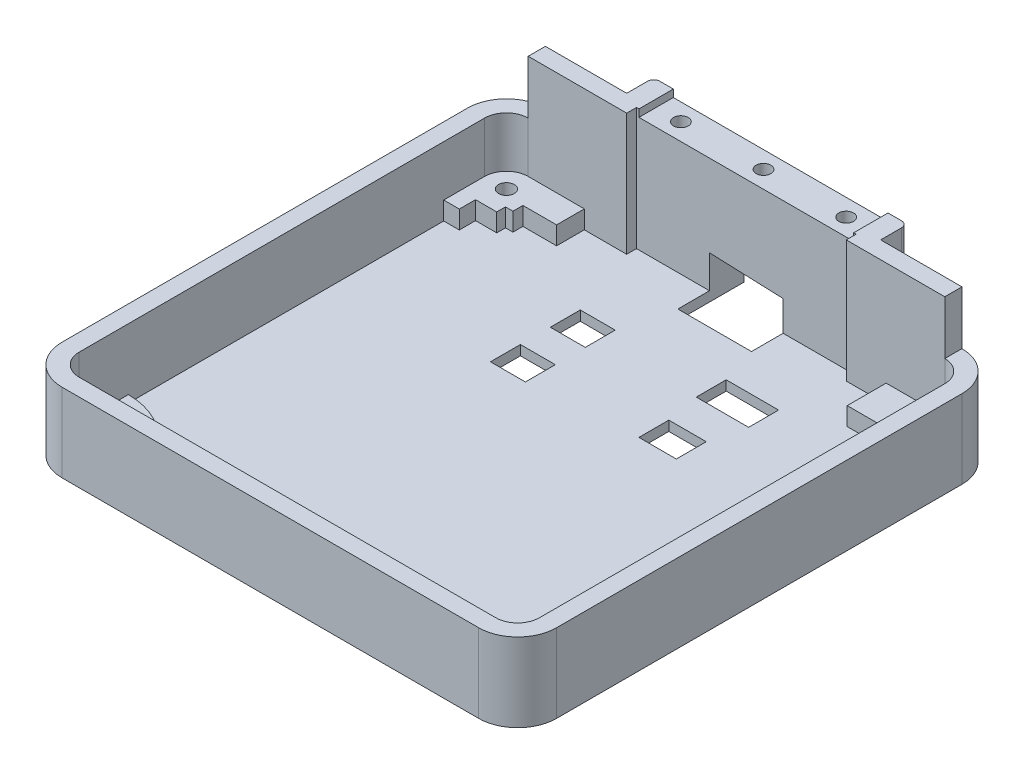
SolidWorks part; units mm, degrees
ref_plane "Front Plane" through (0, 0, 0) normal (0, 0, 1) x (1, 0, 0)
ref_plane "Top Plane" through (0, 0, 0) normal (0, 1, 0) x (1, 0, 0)
ref_plane "Right Plane" through (0, 0, 0) normal (1, 0, 0) x (0, 0, -1)
sketch "Sketch2" plane through (0, 0, 0) normal (0, 1, 0) x (1, 0, 0)
  line L6 (-46.8585, -41.275) -> (-46.8585, 41.275)
  line L8 (46.8585, -41.275) -> (46.8585, 41.275)
  line L9 (42.418, -45.7155) -> (-42.418, -45.7155)
  line L10 (-42.418, 45.7155) -> (-16.8754, 45.7155)
  line L11 (-46.8585, -41.275) -> (-50.3585, -41.275)
  line L14 (-50.3585, -41.275) -> (-50.3585, 41.275)
  line L15 (-42.418, 45.7155) -> (-42.418, 49.2155)
  line L16 (-42.418, 41.275) -> (-37.8452, 38.0373)
  line L17 (-42.418, 49.2155) -> (42.418, 49.2155)
  line L18 (-37.8452, 38.0373) -> (-37.8452, 40.0693)
  line L19 (-37.8452, 40.0693) -> (-30.9872, 40.0693)
  line L20 (-30.9872, 40.0693) -> (-30.9872, 45.7155)
  line L21 (-37.8452, 38.0373) -> (-39.3692, 38.0373)
  line L22 (46.8585, 41.275) -> (50.3585, 41.275)
  line L23 (42.418, -45.7155) -> (42.418, -49.2155)
  line L24 (-39.3692, 38.0373) -> (-39.3692, 36.2593)
  line L25 (42.418, -49.2155) -> (-42.418, -49.2155)
  line L26 (-39.3692, 36.2593) -> (-43.6872, 36.2593)
  line L27 (-43.6872, 36.2593) -> (-43.6872, 32.9573)
  line L28 (50.3585, 41.275) -> (50.3585, -41.275)
  line L34 (-43.6872, 32.9573) -> (-46.8585, 32.9573)
  line L37 (42.418, 41.275) -> (50.0148, 49.9834)
  line L46 (-16.2544, 31.1733) -> (-10.1584, 31.1733)
  line L52 (-10.1584, 31.1733) -> (-10.1584, 25.0773)
  line L58 (-10.1584, 25.0773) -> (-17.2704, 25.0773)
  line L64 (-17.2704, 25.0773) -> (-17.2704, 31.1733)
  line L70 (-17.2704, 31.1733) -> (-16.2544, 31.1733)
  line L76 (-17.2704, 25.0773) -> (-17.2704, 18.9813)
  line L82 (-17.2704, 18.9813) -> (-10.1584, 18.9813)
  line L88 (-10.1584, 18.9813) -> (-10.1584, 12.8853)
  line L94 (-10.1584, 12.8853) -> (-17.2704, 12.8853)
  line L100 (-17.2704, 12.8853) -> (-17.2704, 18.9813)
  line L111 (22.418, 45.7155) -> (42.418, 45.7155)
  line L112 (-10.1584, 31.1733) -> (9.9076, 31.1733)
  line L113 (9.9076, 31.1733) -> (9.9076, 33.7133)
  line L114 (9.9076, 33.7133) -> (20.5756, 33.7133)
  line L115 (20.5756, 33.7133) -> (20.5756, 27.6173)
  line L116 (20.5756, 27.6173) -> (9.9076, 27.6173)
  line L117 (9.9076, 27.6173) -> (9.9076, 31.1733)
  line L118 (9.9076, 27.6173) -> (9.9076, 20.7633)
  line L119 (9.9076, 20.7633) -> (18.7976, 20.7633)
  line L120 (18.7976, 20.7633) -> (18.7976, 14.6673)
  line L121 (18.7976, 14.6673) -> (11.1776, 14.6673)
  line L122 (11.1776, 14.6673) -> (11.1776, 20.7633)
  line L123 (42.418, 41.275) -> (0, 41.275)
  line L124 (42.418, 41.275) -> (39.3704, 37.7815)
  line L125 (39.3704, 37.7815) -> (39.3704, 33.2095)
  line L126 (39.3704, 37.7815) -> (30.4804, 37.7815)
  line L127 (30.4804, 37.7815) -> (30.4804, 45.7155)
  line L128 (39.3704, 33.2095) -> (46.8585, 33.2095)
  line L129 (22.418, 45.7155) -> (-16.8754, 45.7155)
  line L130 (46.8585, -41.275) -> (46.8585, -31.275)
  line L131 (42.418, -45.7155) -> (32.418, -45.7155)
  line L132 (-42.418, -45.7155) -> (-32.418, -45.7155)
  line L133 (-46.8585, -41.275) -> (-46.8585, -31.275)
  arc A0 (-42.418, 45.7155) -> (-46.8585, 41.275) centre (-42.418, 41.275) ccw
  arc A1 (42.418, 45.7155) -> (46.8585, 41.275) centre (42.418, 41.275) cw
  arc A2 (-46.8585, -41.275) -> (-42.418, -45.7155) centre (-42.418, -41.275) ccw
  arc A3 (46.8585, -41.275) -> (42.418, -45.7155) centre (42.418, -41.275) cw
  circle A4 centre (42.418, 41.275) radius 1.6
  circle A5 centre (-42.418, 41.275) radius 1.6
  circle A6 centre (-42.418, -41.275) radius 1.6
  circle A7 centre (42.418, -41.275) radius 1.6
  arc A8 (-42.418, 49.2155) -> (-50.3585, 41.275) centre (-42.418, 41.275) ccw
  arc A9 (42.418, 49.2155) -> (50.3585, 41.275) centre (42.418, 41.275) cw
  arc A10 (42.418, -49.2155) -> (50.3585, -41.275) centre (42.418, -41.275) ccw
  arc A11 (-42.418, -49.2155) -> (-50.3585, -41.275) centre (-42.418, -41.275) cw
  arc A12 (46.8585, -31.275) -> (32.418, -45.7155) centre (46.8585, -45.7155) ccw
  arc A13 (-46.8585, -31.275) -> (-32.418, -45.7155) centre (-46.8585, -45.7155) cw
extrude "Boss-Extrude1" add sketch "Sketch2" along normal blind 1.5 contours L8 A12 L9 A3 A7 | A13 L6 A2 L9 A6 region at (-40.4967, 0, 39.3537) region at (40.4967, 0, 39.3537)
sketch "Sketch5" plane through (0, 0, 0) normal (0, -1, 0) x (1, 0, 0)
  line L0 (-17.2704, -25.0773) -> (-17.2704, -18.9813) construction
  line L1 (42.418, -41.275) -> (50.0148, -49.9834) construction
  line L2 (42.418, -41.275) -> (0, -41.275) construction
  line L3 (42.418, -41.275) -> (39.3704, -37.7815) construction
  line L4 (-42.418, -41.275) -> (-37.8452, -38.0373) construction
  line L5 (-42.418, -45.7155) -> (-16.8754, -45.7155) construction
  line L6 (22.418, -45.7155) -> (-16.8754, -45.7155) construction
  line L7 (22.418, -45.7155) -> (42.418, -45.7155) construction
  line L8 (-42.418, -45.7155) -> (-42.418, -49.2155) construction
  line L9 (-46.8585, 41.275) -> (-46.8585, -41.275) construction
  line L10 (42.418, 45.7155) -> (-42.418, 45.7155) construction
  line L11 (-42.418, 45.7155) -> (-32.418, 45.7155) construction
  line L12 (-46.8585, 41.275) -> (-46.8585, 31.275) construction
  line L13 (42.418, 45.7155) -> (42.418, 49.2155) construction
  line L14 (46.8585, 41.275) -> (46.8585, 31.275) construction
  line L15 (42.418, 45.7155) -> (32.418, 45.7155) construction
  line L16 (46.8585, 41.275) -> (46.8585, -41.275) construction
  line L17 (46.8585, -41.275) -> (50.3585, -41.275) construction
  line L18 (-46.8585, 41.275) -> (-50.3585, 41.275) construction
  line L19 (-37.8452, -38.0373) -> (-39.3692, -38.0373) construction
  line L20 (-39.3692, -38.0373) -> (-39.3692, -36.2593) construction
  line L21 (-39.3692, -36.2593) -> (-43.6872, -36.2593) construction
  line L22 (-43.6872, -36.2593) -> (-43.6872, -32.9573) construction
  line L23 (-43.6872, -32.9573) -> (-46.8585, -32.9573) construction
  line L24 (-37.8452, -38.0373) -> (-37.8452, -40.0693) construction
  line L25 (-37.8452, -40.0693) -> (-30.9872, -40.0693) construction
  line L26 (-30.9872, -40.0693) -> (-30.9872, -45.7155) construction
  line L27 (-42.418, -49.2155) -> (42.418, -49.2155) construction
  line L28 (-50.3585, 41.275) -> (-50.3585, -41.275) construction
  line L29 (42.418, 49.2155) -> (-42.418, 49.2155) construction
  line L30 (9.9076, -31.1733) -> (9.9076, -33.7133) construction
  line L31 (9.9076, -33.7133) -> (20.5756, -33.7133) construction
  line L32 (20.5756, -33.7133) -> (20.5756, -27.6173) construction
  line L33 (20.5756, -27.6173) -> (9.9076, -27.6173) construction
  line L34 (9.9076, -27.6173) -> (9.9076, -31.1733) construction
  line L35 (9.9076, -27.6173) -> (9.9076, -20.7633) construction
  line L36 (9.9076, -20.7633) -> (18.7976, -20.7633) construction
  line L37 (18.7976, -20.7633) -> (18.7976, -14.6673) construction
  line L38 (18.7976, -14.6673) -> (11.1776, -14.6673) construction
  line L39 (11.1776, -14.6673) -> (11.1776, -20.7633) construction
  line L40 (-10.1584, -31.1733) -> (9.9076, -31.1733) construction
  line L41 (50.3585, -41.275) -> (50.3585, 41.275) construction
  line L42 (39.3704, -37.7815) -> (39.3704, -33.2095) construction
  line L43 (39.3704, -33.2095) -> (46.8585, -33.2095) construction
  line L44 (39.3704, -37.7815) -> (30.4804, -37.7815) construction
  line L45 (30.4804, -37.7815) -> (30.4804, -45.7155) construction
  line L46 (-10.1584, -31.1733) -> (-10.1584, -25.0773) construction
  line L47 (-10.1584, -25.0773) -> (-17.2704, -25.0773) construction
  line L48 (-16.2544, -31.1733) -> (-10.1584, -31.1733) construction
  line L49 (-17.2704, -31.1733) -> (-16.2544, -31.1733) construction
  line L50 (-17.2704, -25.0773) -> (-17.2704, -31.1733) construction
  line L51 (-17.2704, -18.9813) -> (-10.1584, -18.9813) construction
  line L52 (-10.1584, -18.9813) -> (-10.1584, -12.8853) construction
  line L53 (-10.1584, -12.8853) -> (-17.2704, -12.8853) construction
  line L54 (-17.2704, -12.8853) -> (-17.2704, -18.9813) construction
  line L55 (-17.2704, -25.0773) -> (-17.2704, -18.9813)
  line L56 (42.418, -41.275) -> (50.0148, -49.9834)
  line L57 (42.418, -41.275) -> (0, -41.275)
  line L58 (42.418, -41.275) -> (39.3704, -37.7815)
  line L59 (-42.418, -41.275) -> (-37.8452, -38.0373)
  line L60 (-42.418, -45.7155) -> (-16.8754, -45.7155)
  line L61 (22.418, -45.7155) -> (-16.8754, -45.7155)
  line L62 (22.418, -45.7155) -> (42.418, -45.7155)
  line L63 (-42.418, -45.7155) -> (-42.418, -49.2155)
  line L64 (-46.8585, 41.275) -> (-46.8585, -41.275)
  line L65 (42.418, 45.7155) -> (-42.418, 45.7155)
  line L66 (-42.418, 45.7155) -> (-32.418, 45.7155)
  line L67 (-46.8585, 41.275) -> (-46.8585, 31.275)
  line L68 (42.418, 45.7155) -> (42.418, 49.2155)
  line L69 (46.8585, 41.275) -> (46.8585, 31.275)
  line L70 (42.418, 45.7155) -> (32.418, 45.7155)
  line L71 (46.8585, 41.275) -> (46.8585, -41.275)
  line L72 (46.8585, -41.275) -> (50.3585, -41.275)
  line L73 (-46.8585, 41.275) -> (-50.3585, 41.275)
  line L74 (-37.8452, -38.0373) -> (-39.3692, -38.0373)
  line L75 (-39.3692, -38.0373) -> (-39.3692, -36.2593)
  line L76 (-39.3692, -36.2593) -> (-43.6872, -36.2593)
  line L77 (-43.6872, -36.2593) -> (-43.6872, -32.9573)
  line L78 (-43.6872, -32.9573) -> (-46.8585, -32.9573)
  line L79 (-37.8452, -38.0373) -> (-37.8452, -40.0693)
  line L80 (-37.8452, -40.0693) -> (-30.9872, -40.0693)
  line L81 (-30.9872, -40.0693) -> (-30.9872, -45.7155)
  line L82 (-42.418, -49.2155) -> (42.418, -49.2155)
  line L83 (-50.3585, 41.275) -> (-50.3585, -41.275)
  line L84 (42.418, 49.2155) -> (-42.418, 49.2155)
  line L85 (9.9076, -31.1733) -> (9.9076, -33.7133)
  line L86 (9.9076, -33.7133) -> (20.5756, -33.7133)
  line L87 (20.5756, -33.7133) -> (20.5756, -27.6173)
  line L88 (20.5756, -27.6173) -> (9.9076, -27.6173)
  line L89 (9.9076, -27.6173) -> (9.9076, -31.1733)
  line L90 (9.9076, -27.6173) -> (9.9076, -20.7633)
  line L91 (9.9076, -20.7633) -> (18.7976, -20.7633)
  line L92 (18.7976, -20.7633) -> (18.7976, -14.6673)
  line L93 (18.7976, -14.6673) -> (11.1776, -14.6673)
  line L94 (11.1776, -14.6673) -> (11.1776, -20.7633)
  line L95 (-10.1584, -31.1733) -> (9.9076, -31.1733)
  line L96 (50.3585, -41.275) -> (50.3585, 41.275)
  line L97 (39.3704, -37.7815) -> (39.3704, -33.2095)
  line L98 (39.3704, -33.2095) -> (46.8585, -33.2095)
  line L99 (39.3704, -37.7815) -> (30.4804, -37.7815)
  line L100 (30.4804, -37.7815) -> (30.4804, -45.7155)
  line L101 (-10.1584, -31.1733) -> (-10.1584, -25.0773)
  line L102 (-10.1584, -25.0773) -> (-17.2704, -25.0773)
  line L103 (-16.2544, -31.1733) -> (-10.1584, -31.1733)
  line L104 (-17.2704, -31.1733) -> (-16.2544, -31.1733)
  line L105 (-17.2704, -25.0773) -> (-17.2704, -31.1733)
  line L106 (-17.2704, -18.9813) -> (-10.1584, -18.9813)
  line L107 (-10.1584, -18.9813) -> (-10.1584, -12.8853)
  line L108 (-10.1584, -12.8853) -> (-17.2704, -12.8853)
  line L109 (-17.2704, -12.8853) -> (-17.2704, -18.9813)
  line L110 (50.3585, -41.275) -> (50.3585, 41.275)
  line L111 (42.418, 49.2155) -> (-42.418, 49.2155)
  line L112 (-50.3585, 41.275) -> (-50.3585, -41.275)
  line L113 (-42.418, -49.2155) -> (42.418, -49.2155)
  arc A0 (42.418, -45.7155) -> (46.8585, -41.275) centre (42.418, -41.275) ccw construction
  arc A1 (-46.8585, -41.275) -> (-42.418, -45.7155) centre (-42.418, -41.275) ccw construction
  arc A2 (-46.8585, 31.275) -> (-32.418, 45.7155) centre (-46.8585, 45.7155) ccw construction
  arc A3 (-42.418, 45.7155) -> (-46.8585, 41.275) centre (-42.418, 41.275) ccw construction
  arc A4 (32.418, 45.7155) -> (46.8585, 31.275) centre (46.8585, 45.7155) ccw construction
  arc A5 (46.8585, 41.275) -> (42.418, 45.7155) centre (42.418, 41.275) ccw construction
  arc A6 (42.418, -49.2155) -> (50.3585, -41.275) centre (42.418, -41.275) ccw construction
  arc A7 (-50.3585, -41.275) -> (-42.418, -49.2155) centre (-42.418, -41.275) ccw construction
  arc A8 (-42.418, 49.2155) -> (-50.3585, 41.275) centre (-42.418, 41.275) ccw construction
  arc A9 (50.3585, 41.275) -> (42.418, 49.2155) centre (42.418, 41.275) ccw construction
  circle A10 centre (42.418, 41.275) radius 1.6 construction
  circle A11 centre (-42.418, 41.275) radius 1.6 construction
  circle A12 centre (-42.418, -41.275) radius 1.6 construction
  circle A13 centre (42.418, -41.275) radius 1.6 construction
  arc A14 (42.418, -45.7155) -> (46.8585, -41.275) centre (42.418, -41.275) ccw
  arc A15 (-46.8585, -41.275) -> (-42.418, -45.7155) centre (-42.418, -41.275) ccw
  arc A16 (-46.8585, 31.275) -> (-32.418, 45.7155) centre (-46.8585, 45.7155) ccw
  arc A17 (-42.418, 45.7155) -> (-46.8585, 41.275) centre (-42.418, 41.275) ccw
  arc A18 (32.418, 45.7155) -> (46.8585, 31.275) centre (46.8585, 45.7155) ccw
  arc A19 (46.8585, 41.275) -> (42.418, 45.7155) centre (42.418, 41.275) ccw
  arc A20 (42.418, -49.2155) -> (50.3585, -41.275) centre (42.418, -41.275) ccw
  arc A21 (-50.3585, -41.275) -> (-42.418, -49.2155) centre (-42.418, -41.275) ccw
  arc A22 (-42.418, 49.2155) -> (-50.3585, 41.275) centre (-42.418, 41.275) ccw
  arc A23 (50.3585, 41.275) -> (42.418, 49.2155) centre (42.418, 41.275) ccw
  circle A24 centre (42.418, 41.275) radius 1.6
  circle A25 centre (-42.418, 41.275) radius 1.6
  circle A26 centre (-42.418, -41.275) radius 1.6
  circle A27 centre (42.418, -41.275) radius 1.6
  arc A28 (42.418, -49.2155) -> (50.3585, -41.275) centre (42.418, -41.275) ccw
  arc A29 (50.3585, 41.275) -> (42.418, 49.2155) centre (42.418, 41.275) ccw
  arc A30 (-42.418, 49.2155) -> (-50.3585, 41.275) centre (-42.418, 41.275) ccw
  arc A31 (-50.3585, -41.275) -> (-42.418, -49.2155) centre (-42.418, -41.275) ccw
  arc M1 (-46.8585, 31.275) -> (-32.418, 45.7155) centre (-46.8585, 45.7155) ccw
  line M2 (-32.418, 45.7155) -> (-42.418, 45.7155)
  arc M3 (-42.418, 45.7155) -> (-46.8585, 41.275) centre (-42.418, 41.275) ccw
  line M4 (-46.8585, 41.275) -> (-46.8585, 31.275)
  circle M5 centre (-42.418, 41.275) radius 1.6
extrude "Boss-Extrude3" add sketch "Sketch5" along normal blind 2 contours L82 A20 L56 A14 L62 L61 L60 L63 | L56 A20 L72 A14 | L96 A23 L68 A19 L69 L71 L72 | A18 L65 L64 L78 L77 L76 L75 L74 L79 L80 L81 L60 L61 L62 L100 L99 L97 L98 L71 L109 L108 L107 L106 L102 L101 L89 L94 L93 L92 L91 L88 L87 L86 L85 L103 L104 L105 M1 | A27 L58 L99 L100 L57 | A27 L57 L100 L62 A14 L56 | A27 L56 A14 L71 L98 L97 L58 | A26 L74 L75 L76 L77 L78 L64 A15 L60 L81 L80 L79 | M4 M1 M2 M3 M5 | L69 A19 L65 A18 A24 | L84 A22 L73 L65 L68 M3 M2 | L83 A21 L63 A15 L64 L73 M4 region at (43.6425, 0, -37.4818) region at (37.0258, 0, -43.6304) region at (35.5464, 0, -39.5753) region at (48.0295, 0, -43.8264) region at (2.2185, 0, -47.4473) region at (-0.2178, 0, 0.4927) region at (48.3825, 0, 4.776) region at (-48.3825, 0, -4.776) region at (40.4967, 0, 39.3537) region at (-39.9913, 0, -40.9811) region at (-4.7781, 0, 47.245) region at (-40.4967, 0, 39.3537)
sketch "Sketch6" plane through (0, 0, 0) normal (0, 1, 0) x (1, 0, 0)
  line L0 (-17.2704, 25.0773) -> (-17.2704, 18.9813) construction
  line L1 (42.418, 41.275) -> (50.0148, 49.9834) construction
  line L2 (42.418, 41.275) -> (0, 41.275) construction
  line L3 (42.418, 41.275) -> (39.3704, 37.7815) construction
  line L4 (-42.418, 41.275) -> (-37.8452, 38.0373) construction
  line L5 (-42.418, 45.7155) -> (-16.8754, 45.7155) construction
  line L6 (22.418, 45.7155) -> (-16.8754, 45.7155) construction
  line L7 (22.418, 45.7155) -> (42.418, 45.7155) construction
  line L8 (-42.418, 45.7155) -> (-42.418, 49.2155) construction
  line L9 (-46.8585, -41.275) -> (-46.8585, 41.275) construction
  line L10 (42.418, -45.7155) -> (-42.418, -45.7155) construction
  line L11 (-42.418, -45.7155) -> (-32.418, -45.7155) construction
  line L12 (-46.8585, -41.275) -> (-46.8585, -31.275) construction
  line L13 (42.418, -45.7155) -> (42.418, -49.2155) construction
  line L14 (46.8585, -41.275) -> (46.8585, -31.275) construction
  line L15 (42.418, -45.7155) -> (32.418, -45.7155) construction
  line L16 (46.8585, -41.275) -> (46.8585, 41.275) construction
  line L17 (46.8585, 41.275) -> (50.3585, 41.275) construction
  line L18 (-46.8585, -41.275) -> (-50.3585, -41.275) construction
  line L19 (-37.8452, 38.0373) -> (-39.3692, 38.0373) construction
  line L20 (-39.3692, 38.0373) -> (-39.3692, 36.2593) construction
  line L21 (-39.3692, 36.2593) -> (-43.6872, 36.2593) construction
  line L22 (-43.6872, 36.2593) -> (-43.6872, 32.9573) construction
  line L23 (-43.6872, 32.9573) -> (-46.8585, 32.9573) construction
  line L24 (-37.8452, 38.0373) -> (-37.8452, 40.0693) construction
  line L25 (-37.8452, 40.0693) -> (-30.9872, 40.0693) construction
  line L26 (-30.9872, 40.0693) -> (-30.9872, 45.7155) construction
  line L27 (-42.418, 49.2155) -> (42.418, 49.2155) construction
  line L28 (-50.3585, -41.275) -> (-50.3585, 41.275) construction
  line L29 (42.418, -49.2155) -> (-42.418, -49.2155) construction
  line L30 (9.9076, 31.1733) -> (9.9076, 33.7133) construction
  line L31 (9.9076, 33.7133) -> (20.5756, 33.7133) construction
  line L32 (20.5756, 33.7133) -> (20.5756, 27.6173) construction
  line L33 (20.5756, 27.6173) -> (9.9076, 27.6173) construction
  line L34 (9.9076, 27.6173) -> (9.9076, 31.1733) construction
  line L35 (9.9076, 27.6173) -> (9.9076, 20.7633) construction
  line L36 (9.9076, 20.7633) -> (18.7976, 20.7633) construction
  line L37 (18.7976, 20.7633) -> (18.7976, 14.6673) construction
  line L38 (18.7976, 14.6673) -> (11.1776, 14.6673) construction
  line L39 (11.1776, 14.6673) -> (11.1776, 20.7633) construction
  line L40 (-10.1584, 31.1733) -> (9.9076, 31.1733) construction
  line L41 (50.3585, 41.275) -> (50.3585, -41.275) construction
  line L42 (39.3704, 37.7815) -> (39.3704, 33.2095) construction
  line L43 (39.3704, 33.2095) -> (46.8585, 33.2095) construction
  line L44 (39.3704, 37.7815) -> (30.4804, 37.7815) construction
  line L45 (30.4804, 37.7815) -> (30.4804, 45.7155) construction
  line L46 (-10.1584, 31.1733) -> (-10.1584, 25.0773) construction
  line L47 (-10.1584, 25.0773) -> (-17.2704, 25.0773) construction
  line L48 (-16.2544, 31.1733) -> (-10.1584, 31.1733) construction
  line L49 (-17.2704, 31.1733) -> (-16.2544, 31.1733) construction
  line L50 (-17.2704, 25.0773) -> (-17.2704, 31.1733) construction
  line L51 (-17.2704, 18.9813) -> (-10.1584, 18.9813) construction
  line L52 (-10.1584, 18.9813) -> (-10.1584, 12.8853) construction
  line L53 (-10.1584, 12.8853) -> (-17.2704, 12.8853) construction
  line L54 (-17.2704, 12.8853) -> (-17.2704, 18.9813) construction
  line L55 (-17.2704, 25.0773) -> (-17.2704, 18.9813)
  line L56 (42.418, 41.275) -> (50.0148, 49.9834)
  line L57 (42.418, 41.275) -> (0, 41.275)
  line L58 (42.418, 41.275) -> (39.3704, 37.7815)
  line L59 (-42.418, 41.275) -> (-37.8452, 38.0373)
  line L60 (-42.418, 45.7155) -> (-16.8754, 45.7155)
  line L61 (22.418, 45.7155) -> (-16.8754, 45.7155)
  line L62 (22.418, 45.7155) -> (42.418, 45.7155)
  line L63 (-42.418, 45.7155) -> (-42.418, 49.2155)
  line L64 (-46.8585, -41.275) -> (-46.8585, 41.275)
  line L65 (42.418, -45.7155) -> (-42.418, -45.7155)
  line L66 (-42.418, -45.7155) -> (-32.418, -45.7155)
  line L67 (-46.8585, -41.275) -> (-46.8585, -31.275)
  line L68 (42.418, -45.7155) -> (42.418, -49.2155)
  line L69 (46.8585, -41.275) -> (46.8585, -31.275)
  line L70 (42.418, -45.7155) -> (32.418, -45.7155)
  line L71 (46.8585, -41.275) -> (46.8585, 41.275)
  line L72 (46.8585, 41.275) -> (50.3585, 41.275)
  line L73 (-46.8585, -41.275) -> (-50.3585, -41.275)
  line L74 (-37.8452, 38.0373) -> (-39.3692, 38.0373)
  line L75 (-39.3692, 38.0373) -> (-39.3692, 36.2593)
  line L76 (-39.3692, 36.2593) -> (-43.6872, 36.2593)
  line L77 (-43.6872, 36.2593) -> (-43.6872, 32.9573)
  line L78 (-43.6872, 32.9573) -> (-46.8585, 32.9573)
  line L79 (-37.8452, 38.0373) -> (-37.8452, 40.0693)
  line L80 (-37.8452, 40.0693) -> (-30.9872, 40.0693)
  line L81 (-30.9872, 40.0693) -> (-30.9872, 45.7155)
  line L82 (-42.418, 49.2155) -> (42.418, 49.2155)
  line L83 (-50.3585, -41.275) -> (-50.3585, 41.275)
  line L84 (42.418, -49.2155) -> (-42.418, -49.2155)
  line L85 (9.9076, 31.1733) -> (9.9076, 33.7133)
  line L86 (9.9076, 33.7133) -> (20.5756, 33.7133)
  line L87 (20.5756, 33.7133) -> (20.5756, 27.6173)
  line L88 (20.5756, 27.6173) -> (9.9076, 27.6173)
  line L89 (9.9076, 27.6173) -> (9.9076, 31.1733)
  line L90 (9.9076, 27.6173) -> (9.9076, 20.7633)
  line L91 (9.9076, 20.7633) -> (18.7976, 20.7633)
  line L92 (18.7976, 20.7633) -> (18.7976, 14.6673)
  line L93 (18.7976, 14.6673) -> (11.1776, 14.6673)
  line L94 (11.1776, 14.6673) -> (11.1776, 20.7633)
  line L95 (-10.1584, 31.1733) -> (9.9076, 31.1733)
  line L96 (50.3585, 41.275) -> (50.3585, -41.275)
  line L97 (39.3704, 37.7815) -> (39.3704, 33.2095)
  line L98 (39.3704, 33.2095) -> (46.8585, 33.2095)
  line L99 (39.3704, 37.7815) -> (30.4804, 37.7815)
  line L100 (30.4804, 37.7815) -> (30.4804, 45.7155)
  line L101 (-10.1584, 31.1733) -> (-10.1584, 25.0773)
  line L102 (-10.1584, 25.0773) -> (-17.2704, 25.0773)
  line L103 (-16.2544, 31.1733) -> (-10.1584, 31.1733)
  line L104 (-17.2704, 31.1733) -> (-16.2544, 31.1733)
  line L105 (-17.2704, 25.0773) -> (-17.2704, 31.1733)
  line L106 (-17.2704, 18.9813) -> (-10.1584, 18.9813)
  line L107 (-10.1584, 18.9813) -> (-10.1584, 12.8853)
  line L108 (-10.1584, 12.8853) -> (-17.2704, 12.8853)
  line L109 (-17.2704, 12.8853) -> (-17.2704, 18.9813)
  line L110 (30.4804, 45.7155) -> (30.4804, 37.7815)
  line L111 (39.3704, 37.7815) -> (39.3704, 33.2095)
  line L112 (30.4804, 37.7815) -> (39.3704, 37.7815)
  line L113 (39.3704, 33.2095) -> (46.8585, 33.2095)
  line L114 (46.8585, 33.2095) -> (46.8585, 41.275)
  line L115 (42.418, 45.7155) -> (30.4804, 45.7155)
  line L116 (-42.418, 45.7155) -> (-30.9872, 45.7155)
  line L117 (-30.9872, 45.7155) -> (-30.9872, 40.0693)
  line L118 (-30.9872, 40.0693) -> (-37.8452, 40.0693)
  line L119 (-37.8452, 40.0693) -> (-37.8452, 38.0373)
  line L120 (-37.8452, 38.0373) -> (-39.3692, 38.0373)
  line L121 (-39.3692, 38.0373) -> (-39.3692, 36.2593)
  line L122 (-39.3692, 36.2593) -> (-43.6872, 36.2593)
  line L123 (-43.6872, 36.2593) -> (-43.6872, 32.9573)
  line L124 (-43.6872, 32.9573) -> (-46.8585, 32.9573)
  line L125 (-46.8585, 32.9573) -> (-46.8585, 41.275)
  arc A0 (46.8585, 41.275) -> (42.418, 45.7155) centre (42.418, 41.275) ccw construction
  arc A1 (-42.418, 45.7155) -> (-46.8585, 41.275) centre (-42.418, 41.275) ccw construction
  arc A2 (-32.418, -45.7155) -> (-46.8585, -31.275) centre (-46.8585, -45.7155) ccw construction
  arc A3 (-46.8585, -41.275) -> (-42.418, -45.7155) centre (-42.418, -41.275) ccw construction
  arc A4 (46.8585, -31.275) -> (32.418, -45.7155) centre (46.8585, -45.7155) ccw construction
  arc A5 (42.418, -45.7155) -> (46.8585, -41.275) centre (42.418, -41.275) ccw construction
  arc A6 (50.3585, 41.275) -> (42.418, 49.2155) centre (42.418, 41.275) ccw construction
  arc A7 (-42.418, 49.2155) -> (-50.3585, 41.275) centre (-42.418, 41.275) ccw construction
  arc A8 (-50.3585, -41.275) -> (-42.418, -49.2155) centre (-42.418, -41.275) ccw construction
  arc A9 (42.418, -49.2155) -> (50.3585, -41.275) centre (42.418, -41.275) ccw construction
  circle A10 centre (42.418, -41.275) radius 1.6 construction
  circle A11 centre (-42.418, -41.275) radius 1.6 construction
  circle A12 centre (-42.418, 41.275) radius 1.6 construction
  circle A13 centre (42.418, 41.275) radius 1.6 construction
  arc A14 (46.8585, 41.275) -> (42.418, 45.7155) centre (42.418, 41.275) ccw
  arc A15 (-42.418, 45.7155) -> (-46.8585, 41.275) centre (-42.418, 41.275) ccw
  arc A16 (-32.418, -45.7155) -> (-46.8585, -31.275) centre (-46.8585, -45.7155) ccw
  arc A17 (-46.8585, -41.275) -> (-42.418, -45.7155) centre (-42.418, -41.275) ccw
  arc A18 (46.8585, -31.275) -> (32.418, -45.7155) centre (46.8585, -45.7155) ccw
  arc A19 (42.418, -45.7155) -> (46.8585, -41.275) centre (42.418, -41.275) ccw
  arc A20 (50.3585, 41.275) -> (42.418, 49.2155) centre (42.418, 41.275) ccw
  arc A21 (-42.418, 49.2155) -> (-50.3585, 41.275) centre (-42.418, 41.275) ccw
  arc A22 (-50.3585, -41.275) -> (-42.418, -49.2155) centre (-42.418, -41.275) ccw
  arc A23 (42.418, -49.2155) -> (50.3585, -41.275) centre (42.418, -41.275) ccw
  circle A24 centre (42.418, -41.275) radius 1.6
  circle A25 centre (-42.418, -41.275) radius 1.6
  circle A26 centre (-42.418, 41.275) radius 1.6
  circle A27 centre (42.418, 41.275) radius 1.6
  arc A28 (-46.8585, 41.275) -> (-42.418, 45.7155) centre (-42.418, 41.275) cw
  arc A29 (46.8585, 41.275) -> (42.418, 45.7155) centre (42.418, 41.275) ccw
  circle M17 centre (42.418, 41.275) radius 1.6
  circle M34 centre (-42.418, 41.275) radius 1.6
extrude "Boss-Extrude4" add sketch "Sketch6" along normal blind 3.7 contours L56 A14 L62 L100 L57 M17 | L100 L99 L58 L57 M17 | L71 A14 L56 L58 L97 L98 M17 | L60 A15 L64 L78 L77 L76 L75 L74 L79 L80 L81 M34 region at (37.0258, 0, -43.6304) region at (43.6425, 0, -37.4818) region at (35.5464, 0, -39.5753) region at (-39.9913, 0, -40.9811)
sketch "Sketch7" plane through (0, 0, 0) normal (0, 1, 0) x (1, 0, 0)
  line L0 (-17.2704, 25.0773) -> (-17.2704, 18.9813) construction
  line L1 (42.418, 41.275) -> (50.0148, 49.9834) construction
  line L2 (42.418, 41.275) -> (0, 41.275) construction
  line L3 (42.418, 41.275) -> (39.3704, 37.7815) construction
  line L4 (-42.418, 41.275) -> (-37.8452, 38.0373) construction
  line L5 (-42.418, 45.7155) -> (-16.8754, 45.7155) construction
  line L6 (22.418, 45.7155) -> (-16.8754, 45.7155) construction
  line L7 (22.418, 45.7155) -> (42.418, 45.7155) construction
  line L8 (-42.418, 45.7155) -> (-42.418, 49.2155) construction
  line L9 (-46.8585, -41.275) -> (-46.8585, 41.275) construction
  line L10 (42.418, -45.7155) -> (-42.418, -45.7155) construction
  line L11 (-42.418, -45.7155) -> (-32.418, -45.7155) construction
  line L12 (-46.8585, -41.275) -> (-46.8585, -31.275) construction
  line L13 (42.418, -45.7155) -> (42.418, -49.2155) construction
  line L14 (46.8585, -41.275) -> (46.8585, -31.275) construction
  line L15 (42.418, -45.7155) -> (32.418, -45.7155) construction
  line L16 (46.8585, -41.275) -> (46.8585, 41.275) construction
  line L17 (46.8585, 41.275) -> (50.3585, 41.275) construction
  line L18 (-46.8585, -41.275) -> (-50.3585, -41.275) construction
  line L19 (-37.8452, 38.0373) -> (-39.3692, 38.0373) construction
  line L20 (-39.3692, 38.0373) -> (-39.3692, 36.2593) construction
  line L21 (-39.3692, 36.2593) -> (-43.6872, 36.2593) construction
  line L22 (-43.6872, 36.2593) -> (-43.6872, 32.9573) construction
  line L23 (-43.6872, 32.9573) -> (-46.8585, 32.9573) construction
  line L24 (-37.8452, 38.0373) -> (-37.8452, 40.0693) construction
  line L25 (-37.8452, 40.0693) -> (-30.9872, 40.0693) construction
  line L26 (-30.9872, 40.0693) -> (-30.9872, 45.7155) construction
  line L27 (-42.418, 49.2155) -> (42.418, 49.2155) construction
  line L28 (-50.3585, -41.275) -> (-50.3585, 41.275) construction
  line L29 (42.418, -49.2155) -> (-42.418, -49.2155) construction
  line L30 (9.9076, 31.1733) -> (9.9076, 33.7133) construction
  line L31 (9.9076, 33.7133) -> (20.5756, 33.7133) construction
  line L32 (20.5756, 33.7133) -> (20.5756, 27.6173) construction
  line L33 (20.5756, 27.6173) -> (9.9076, 27.6173) construction
  line L34 (9.9076, 27.6173) -> (9.9076, 31.1733) construction
  line L35 (9.9076, 27.6173) -> (9.9076, 20.7633) construction
  line L36 (9.9076, 20.7633) -> (18.7976, 20.7633) construction
  line L37 (18.7976, 20.7633) -> (18.7976, 14.6673) construction
  line L38 (18.7976, 14.6673) -> (11.1776, 14.6673) construction
  line L39 (11.1776, 14.6673) -> (11.1776, 20.7633) construction
  line L40 (-10.1584, 31.1733) -> (9.9076, 31.1733) construction
  line L41 (50.3585, 41.275) -> (50.3585, -41.275) construction
  line L42 (39.3704, 37.7815) -> (39.3704, 33.2095) construction
  line L43 (39.3704, 33.2095) -> (46.8585, 33.2095) construction
  line L44 (39.3704, 37.7815) -> (30.4804, 37.7815) construction
  line L45 (30.4804, 37.7815) -> (30.4804, 45.7155) construction
  line L46 (-10.1584, 31.1733) -> (-10.1584, 25.0773) construction
  line L47 (-10.1584, 25.0773) -> (-17.2704, 25.0773) construction
  line L48 (-16.2544, 31.1733) -> (-10.1584, 31.1733) construction
  line L49 (-17.2704, 31.1733) -> (-16.2544, 31.1733) construction
  line L50 (-17.2704, 25.0773) -> (-17.2704, 31.1733) construction
  line L51 (-17.2704, 18.9813) -> (-10.1584, 18.9813) construction
  line L52 (-10.1584, 18.9813) -> (-10.1584, 12.8853) construction
  line L53 (-10.1584, 12.8853) -> (-17.2704, 12.8853) construction
  line L54 (-17.2704, 12.8853) -> (-17.2704, 18.9813) construction
  line L55 (-17.2704, 25.0773) -> (-17.2704, 18.9813)
  line L56 (42.418, 41.275) -> (50.0148, 49.9834)
  line L57 (42.418, 41.275) -> (0, 41.275)
  line L58 (42.418, 41.275) -> (39.3704, 37.7815)
  line L59 (-42.418, 41.275) -> (-37.8452, 38.0373)
  line L60 (-42.418, 45.7155) -> (-16.8754, 45.7155)
  line L61 (22.418, 45.7155) -> (-16.8754, 45.7155)
  line L62 (22.418, 45.7155) -> (42.418, 45.7155)
  line L63 (-42.418, 45.7155) -> (-42.418, 49.2155)
  line L64 (-46.8585, -41.275) -> (-46.8585, 41.275)
  line L65 (42.418, -45.7155) -> (-42.418, -45.7155)
  line L66 (-42.418, -45.7155) -> (-32.418, -45.7155)
  line L67 (-46.8585, -41.275) -> (-46.8585, -31.275)
  line L68 (42.418, -45.7155) -> (42.418, -49.2155)
  line L69 (46.8585, -41.275) -> (46.8585, -31.275)
  line L70 (42.418, -45.7155) -> (32.418, -45.7155)
  line L71 (46.8585, -41.275) -> (46.8585, 41.275)
  line L72 (46.8585, 41.275) -> (50.3585, 41.275)
  line L73 (-46.8585, -41.275) -> (-50.3585, -41.275)
  line L74 (-37.8452, 38.0373) -> (-39.3692, 38.0373)
  line L75 (-39.3692, 38.0373) -> (-39.3692, 36.2593)
  line L76 (-39.3692, 36.2593) -> (-43.6872, 36.2593)
  line L77 (-43.6872, 36.2593) -> (-43.6872, 32.9573)
  line L78 (-43.6872, 32.9573) -> (-46.8585, 32.9573)
  line L79 (-37.8452, 38.0373) -> (-37.8452, 40.0693)
  line L80 (-37.8452, 40.0693) -> (-30.9872, 40.0693)
  line L81 (-30.9872, 40.0693) -> (-30.9872, 45.7155)
  line L82 (-42.418, 49.2155) -> (42.418, 49.2155)
  line L83 (-50.3585, -41.275) -> (-50.3585, 41.275)
  line L84 (42.418, -49.2155) -> (-42.418, -49.2155)
  line L85 (9.9076, 31.1733) -> (9.9076, 33.7133)
  line L86 (9.9076, 33.7133) -> (20.5756, 33.7133)
  line L87 (20.5756, 33.7133) -> (20.5756, 27.6173)
  line L88 (20.5756, 27.6173) -> (9.9076, 27.6173)
  line L89 (9.9076, 27.6173) -> (9.9076, 31.1733)
  line L90 (9.9076, 27.6173) -> (9.9076, 20.7633)
  line L91 (9.9076, 20.7633) -> (18.7976, 20.7633)
  line L92 (18.7976, 20.7633) -> (18.7976, 14.6673)
  line L93 (18.7976, 14.6673) -> (11.1776, 14.6673)
  line L94 (11.1776, 14.6673) -> (11.1776, 20.7633)
  line L95 (-10.1584, 31.1733) -> (9.9076, 31.1733)
  line L96 (50.3585, 41.275) -> (50.3585, -41.275)
  line L97 (39.3704, 37.7815) -> (39.3704, 33.2095)
  line L98 (39.3704, 33.2095) -> (46.8585, 33.2095)
  line L99 (39.3704, 37.7815) -> (30.4804, 37.7815)
  line L100 (30.4804, 37.7815) -> (30.4804, 45.7155)
  line L101 (-10.1584, 31.1733) -> (-10.1584, 25.0773)
  line L102 (-10.1584, 25.0773) -> (-17.2704, 25.0773)
  line L103 (-16.2544, 31.1733) -> (-10.1584, 31.1733)
  line L104 (-17.2704, 31.1733) -> (-16.2544, 31.1733)
  line L105 (-17.2704, 25.0773) -> (-17.2704, 31.1733)
  line L106 (-17.2704, 18.9813) -> (-10.1584, 18.9813)
  line L107 (-10.1584, 18.9813) -> (-10.1584, 12.8853)
  line L108 (-10.1584, 12.8853) -> (-17.2704, 12.8853)
  line L109 (-17.2704, 12.8853) -> (-17.2704, 18.9813)
  line L110 (0, 41.275) -> (-7.5, 41.275)
  line L111 (0, 41.275) -> (7.5, 41.275)
  line L112 (7.5, 41.275) -> (7.5, 49.2155)
  line L113 (-7.5, 41.275) -> (-7.5, 49.2155)
  arc A0 (46.8585, 41.275) -> (42.418, 45.7155) centre (42.418, 41.275) ccw construction
  arc A1 (-42.418, 45.7155) -> (-46.8585, 41.275) centre (-42.418, 41.275) ccw construction
  arc A2 (-32.418, -45.7155) -> (-46.8585, -31.275) centre (-46.8585, -45.7155) ccw construction
  arc A3 (-46.8585, -41.275) -> (-42.418, -45.7155) centre (-42.418, -41.275) ccw construction
  arc A4 (46.8585, -31.275) -> (32.418, -45.7155) centre (46.8585, -45.7155) ccw construction
  arc A5 (42.418, -45.7155) -> (46.8585, -41.275) centre (42.418, -41.275) ccw construction
  arc A6 (50.3585, 41.275) -> (42.418, 49.2155) centre (42.418, 41.275) ccw construction
  arc A7 (-42.418, 49.2155) -> (-50.3585, 41.275) centre (-42.418, 41.275) ccw construction
  arc A8 (-50.3585, -41.275) -> (-42.418, -49.2155) centre (-42.418, -41.275) ccw construction
  arc A9 (42.418, -49.2155) -> (50.3585, -41.275) centre (42.418, -41.275) ccw construction
  circle A10 centre (42.418, -41.275) radius 1.6 construction
  circle A11 centre (-42.418, -41.275) radius 1.6 construction
  circle A12 centre (-42.418, 41.275) radius 1.6 construction
  circle A13 centre (42.418, 41.275) radius 1.6 construction
  arc A14 (46.8585, 41.275) -> (42.418, 45.7155) centre (42.418, 41.275) ccw
  arc A15 (-42.418, 45.7155) -> (-46.8585, 41.275) centre (-42.418, 41.275) ccw
  arc A16 (-32.418, -45.7155) -> (-46.8585, -31.275) centre (-46.8585, -45.7155) ccw
  arc A17 (-46.8585, -41.275) -> (-42.418, -45.7155) centre (-42.418, -41.275) ccw
  arc A18 (46.8585, -31.275) -> (32.418, -45.7155) centre (46.8585, -45.7155) ccw
  arc A19 (42.418, -45.7155) -> (46.8585, -41.275) centre (42.418, -41.275) ccw
  arc A20 (50.3585, 41.275) -> (42.418, 49.2155) centre (42.418, 41.275) ccw
  arc A21 (-42.418, 49.2155) -> (-50.3585, 41.275) centre (-42.418, 41.275) ccw
  arc A22 (-50.3585, -41.275) -> (-42.418, -49.2155) centre (-42.418, -41.275) ccw
  arc A23 (42.418, -49.2155) -> (50.3585, -41.275) centre (42.418, -41.275) ccw
  circle A24 centre (42.418, -41.275) radius 1.6
  circle A25 centre (-42.418, -41.275) radius 1.6
  circle A26 centre (-42.418, 41.275) radius 1.6
  circle A27 centre (42.418, 41.275) radius 1.6
extrude "Cut-Extrude1" cut sketch "Sketch7" against normal blind 18.7 contours L113 L61 L112 L82 | L113 L110 L57 L112 L61 region at (0, 0, -43.4953) region at (0, 0, -47.4655)
sketch "Sketch8" plane through (0, 0, 0) normal (0, 1, 0) x (1, 0, 0)
  line L0 (-17.2704, 25.0773) -> (-17.2704, 18.9813) construction
  line L1 (42.418, 41.275) -> (50.0148, 49.9834) construction
  line L2 (42.418, 41.275) -> (0, 41.275) construction
  line L3 (42.418, 41.275) -> (39.3704, 37.7815) construction
  line L4 (-42.418, 41.275) -> (-37.8452, 38.0373) construction
  line L5 (-42.418, 45.7155) -> (-16.8754, 45.7155) construction
  line L6 (22.418, 45.7155) -> (-16.8754, 45.7155) construction
  line L7 (22.418, 45.7155) -> (42.418, 45.7155) construction
  line L8 (-42.418, 45.7155) -> (-42.418, 49.2155) construction
  line L9 (-46.8585, -41.275) -> (-46.8585, 41.275) construction
  line L10 (42.418, -45.7155) -> (-42.418, -45.7155) construction
  line L11 (-42.418, -45.7155) -> (-32.418, -45.7155) construction
  line L12 (-46.8585, -41.275) -> (-46.8585, -31.275) construction
  line L13 (42.418, -45.7155) -> (42.418, -49.2155) construction
  line L14 (46.8585, -41.275) -> (46.8585, -31.275) construction
  line L15 (42.418, -45.7155) -> (32.418, -45.7155) construction
  line L16 (46.8585, -41.275) -> (46.8585, 41.275) construction
  line L17 (46.8585, 41.275) -> (50.3585, 41.275) construction
  line L18 (-46.8585, -41.275) -> (-50.3585, -41.275) construction
  line L19 (-37.8452, 38.0373) -> (-39.3692, 38.0373) construction
  line L20 (-39.3692, 38.0373) -> (-39.3692, 36.2593) construction
  line L21 (-39.3692, 36.2593) -> (-43.6872, 36.2593) construction
  line L22 (-43.6872, 36.2593) -> (-43.6872, 32.9573) construction
  line L23 (-43.6872, 32.9573) -> (-46.8585, 32.9573) construction
  line L24 (-37.8452, 38.0373) -> (-37.8452, 40.0693) construction
  line L25 (-37.8452, 40.0693) -> (-30.9872, 40.0693) construction
  line L26 (-30.9872, 40.0693) -> (-30.9872, 45.7155) construction
  line L27 (-42.418, 49.2155) -> (42.418, 49.2155) construction
  line L28 (-50.3585, -41.275) -> (-50.3585, 41.275) construction
  line L29 (42.418, -49.2155) -> (-42.418, -49.2155) construction
  line L30 (9.9076, 31.1733) -> (9.9076, 33.7133) construction
  line L31 (9.9076, 33.7133) -> (20.5756, 33.7133) construction
  line L32 (20.5756, 33.7133) -> (20.5756, 27.6173) construction
  line L33 (20.5756, 27.6173) -> (9.9076, 27.6173) construction
  line L34 (9.9076, 27.6173) -> (9.9076, 31.1733) construction
  line L35 (9.9076, 27.6173) -> (9.9076, 20.7633) construction
  line L36 (9.9076, 20.7633) -> (18.7976, 20.7633) construction
  line L37 (18.7976, 20.7633) -> (18.7976, 14.6673) construction
  line L38 (18.7976, 14.6673) -> (11.1776, 14.6673) construction
  line L39 (11.1776, 14.6673) -> (11.1776, 20.7633) construction
  line L40 (-10.1584, 31.1733) -> (9.9076, 31.1733) construction
  line L41 (50.3585, 41.275) -> (50.3585, -41.275) construction
  line L42 (39.3704, 37.7815) -> (39.3704, 33.2095) construction
  line L43 (39.3704, 33.2095) -> (46.8585, 33.2095) construction
  line L44 (39.3704, 37.7815) -> (30.4804, 37.7815) construction
  line L45 (30.4804, 37.7815) -> (30.4804, 45.7155) construction
  line L46 (-10.1584, 31.1733) -> (-10.1584, 25.0773) construction
  line L47 (-10.1584, 25.0773) -> (-17.2704, 25.0773) construction
  line L48 (-16.2544, 31.1733) -> (-10.1584, 31.1733) construction
  line L49 (-17.2704, 31.1733) -> (-16.2544, 31.1733) construction
  line L50 (-17.2704, 25.0773) -> (-17.2704, 31.1733) construction
  line L51 (-17.2704, 18.9813) -> (-10.1584, 18.9813) construction
  line L52 (-10.1584, 18.9813) -> (-10.1584, 12.8853) construction
  line L53 (-10.1584, 12.8853) -> (-17.2704, 12.8853) construction
  line L54 (-17.2704, 12.8853) -> (-17.2704, 18.9813) construction
  line L55 (-17.2704, 25.0773) -> (-17.2704, 18.9813)
  line L56 (42.418, 41.275) -> (50.0148, 49.9834)
  line L57 (42.418, 41.275) -> (0, 41.275)
  line L58 (42.418, 41.275) -> (39.3704, 37.7815)
  line L59 (-42.418, 41.275) -> (-37.8452, 38.0373)
  line L60 (-42.418, 45.7155) -> (-16.8754, 45.7155)
  line L61 (22.418, 45.7155) -> (-16.8754, 45.7155)
  line L62 (22.418, 45.7155) -> (42.418, 45.7155)
  line L63 (-42.418, 45.7155) -> (-42.418, 49.2155)
  line L64 (-46.8585, -41.275) -> (-46.8585, 41.275)
  line L65 (42.418, -45.7155) -> (-42.418, -45.7155)
  line L66 (-42.418, -45.7155) -> (-32.418, -45.7155)
  line L67 (-46.8585, -41.275) -> (-46.8585, -31.275)
  line L68 (42.418, -45.7155) -> (42.418, -49.2155)
  line L69 (46.8585, -41.275) -> (46.8585, -31.275)
  line L70 (42.418, -45.7155) -> (32.418, -45.7155)
  line L71 (46.8585, -41.275) -> (46.8585, 41.275)
  line L72 (46.8585, 41.275) -> (50.3585, 41.275)
  line L73 (-46.8585, -41.275) -> (-50.3585, -41.275)
  line L74 (-37.8452, 38.0373) -> (-39.3692, 38.0373)
  line L75 (-39.3692, 38.0373) -> (-39.3692, 36.2593)
  line L76 (-39.3692, 36.2593) -> (-43.6872, 36.2593)
  line L77 (-43.6872, 36.2593) -> (-43.6872, 32.9573)
  line L78 (-43.6872, 32.9573) -> (-46.8585, 32.9573)
  line L79 (-37.8452, 38.0373) -> (-37.8452, 40.0693)
  line L80 (-37.8452, 40.0693) -> (-30.9872, 40.0693)
  line L81 (-30.9872, 40.0693) -> (-30.9872, 45.7155)
  line L82 (-42.418, 49.2155) -> (42.418, 49.2155)
  line L83 (-50.3585, -41.275) -> (-50.3585, 41.275)
  line L84 (42.418, -49.2155) -> (-42.418, -49.2155)
  line L85 (9.9076, 31.1733) -> (9.9076, 33.7133)
  line L86 (9.9076, 33.7133) -> (20.5756, 33.7133)
  line L87 (20.5756, 33.7133) -> (20.5756, 27.6173)
  line L88 (20.5756, 27.6173) -> (9.9076, 27.6173)
  line L89 (9.9076, 27.6173) -> (9.9076, 31.1733)
  line L90 (9.9076, 27.6173) -> (9.9076, 20.7633)
  line L91 (9.9076, 20.7633) -> (18.7976, 20.7633)
  line L92 (18.7976, 20.7633) -> (18.7976, 14.6673)
  line L93 (18.7976, 14.6673) -> (11.1776, 14.6673)
  line L94 (11.1776, 14.6673) -> (11.1776, 20.7633)
  line L95 (-10.1584, 31.1733) -> (9.9076, 31.1733)
  line L96 (50.3585, 41.275) -> (50.3585, -41.275)
  line L97 (39.3704, 37.7815) -> (39.3704, 33.2095)
  line L98 (39.3704, 33.2095) -> (46.8585, 33.2095)
  line L99 (39.3704, 37.7815) -> (30.4804, 37.7815)
  line L100 (30.4804, 37.7815) -> (30.4804, 45.7155)
  line L101 (-10.1584, 31.1733) -> (-10.1584, 25.0773)
  line L102 (-10.1584, 25.0773) -> (-17.2704, 25.0773)
  line L103 (-16.2544, 31.1733) -> (-10.1584, 31.1733)
  line L104 (-17.2704, 31.1733) -> (-16.2544, 31.1733)
  line L105 (-17.2704, 25.0773) -> (-17.2704, 31.1733)
  line L106 (-17.2704, 18.9813) -> (-10.1584, 18.9813)
  line L107 (-10.1584, 18.9813) -> (-10.1584, 12.8853)
  line L108 (-10.1584, 12.8853) -> (-17.2704, 12.8853)
  line L109 (-17.2704, 12.8853) -> (-17.2704, 18.9813)
  line L110 (-50.3585, -41.275) -> (-50.3585, 41.275)
  line L111 (-42.418, -49.2155) -> (42.418, -49.2155)
  line L112 (50.3585, -41.275) -> (50.3585, 41.275)
  line L113 (42.418, 49.2155) -> (-42.418, 49.2155)
  line L114 (-50.3585, 41.275) -> (-50.3585, -41.275)
  line L115 (-42.418, -45.7155) -> (42.418, -45.7155)
  line L116 (46.8585, -41.275) -> (46.8585, 41.275)
  line L117 (42.418, 45.7155) -> (-42.418, 45.7155)
  line L118 (-46.8585, 41.275) -> (-46.8585, -41.275)
  arc A0 (46.8585, 41.275) -> (42.418, 45.7155) centre (42.418, 41.275) ccw construction
  arc A1 (-42.418, 45.7155) -> (-46.8585, 41.275) centre (-42.418, 41.275) ccw construction
  arc A2 (-32.418, -45.7155) -> (-46.8585, -31.275) centre (-46.8585, -45.7155) ccw construction
  arc A3 (-46.8585, -41.275) -> (-42.418, -45.7155) centre (-42.418, -41.275) ccw construction
  arc A4 (46.8585, -31.275) -> (32.418, -45.7155) centre (46.8585, -45.7155) ccw construction
  arc A5 (42.418, -45.7155) -> (46.8585, -41.275) centre (42.418, -41.275) ccw construction
  arc A6 (50.3585, 41.275) -> (42.418, 49.2155) centre (42.418, 41.275) ccw construction
  arc A7 (-42.418, 49.2155) -> (-50.3585, 41.275) centre (-42.418, 41.275) ccw construction
  arc A8 (-50.3585, -41.275) -> (-42.418, -49.2155) centre (-42.418, -41.275) ccw construction
  arc A9 (42.418, -49.2155) -> (50.3585, -41.275) centre (42.418, -41.275) ccw construction
  circle A10 centre (42.418, -41.275) radius 1.6 construction
  circle A11 centre (-42.418, -41.275) radius 1.6 construction
  circle A12 centre (-42.418, 41.275) radius 1.6 construction
  circle A13 centre (42.418, 41.275) radius 1.6 construction
  arc A14 (46.8585, 41.275) -> (42.418, 45.7155) centre (42.418, 41.275) ccw
  arc A15 (-42.418, 45.7155) -> (-46.8585, 41.275) centre (-42.418, 41.275) ccw
  arc A16 (-32.418, -45.7155) -> (-46.8585, -31.275) centre (-46.8585, -45.7155) ccw
  arc A17 (-46.8585, -41.275) -> (-42.418, -45.7155) centre (-42.418, -41.275) ccw
  arc A18 (46.8585, -31.275) -> (32.418, -45.7155) centre (46.8585, -45.7155) ccw
  arc A19 (42.418, -45.7155) -> (46.8585, -41.275) centre (42.418, -41.275) ccw
  arc A20 (50.3585, 41.275) -> (42.418, 49.2155) centre (42.418, 41.275) ccw
  arc A21 (-42.418, 49.2155) -> (-50.3585, 41.275) centre (-42.418, 41.275) ccw
  arc A22 (-50.3585, -41.275) -> (-42.418, -49.2155) centre (-42.418, -41.275) ccw
  arc A23 (42.418, -49.2155) -> (50.3585, -41.275) centre (42.418, -41.275) ccw
  circle A24 centre (42.418, -41.275) radius 1.6
  circle A25 centre (-42.418, -41.275) radius 1.6
  circle A26 centre (-42.418, 41.275) radius 1.6
  circle A27 centre (42.418, 41.275) radius 1.6
  arc A28 (-46.8585, -41.275) -> (-42.418, -45.7155) centre (-42.418, -41.275) ccw
  arc A29 (42.418, -45.7155) -> (46.8585, -41.275) centre (42.418, -41.275) ccw
  arc A30 (46.8585, 41.275) -> (42.418, 45.7155) centre (42.418, 41.275) ccw
  arc A31 (-42.418, 45.7155) -> (-46.8585, 41.275) centre (-42.418, 41.275) ccw
  arc A32 (-50.3585, -41.275) -> (-42.418, -49.2155) centre (-42.418, -41.275) ccw
  arc A33 (42.418, -49.2155) -> (50.3585, -41.275) centre (42.418, -41.275) ccw
  arc A34 (50.3585, 41.275) -> (42.418, 49.2155) centre (42.418, 41.275) ccw
  arc A35 (-42.418, 49.2155) -> (-50.3585, 41.275) centre (-42.418, 41.275) ccw
extrude "Boss-Extrude5" add sketch "Sketch8" along normal blind 14 contours L63 A21 L83 L73 L64 A15 | L73 A22 L84 L68 L65 A17 | L68 A23 L96 L72 L71 L69 A19 | L56 A20 L82 L63 L60 L61 L62 A14 | L72 A20 L56 A14 region at (2.2185, 0, -47.4473) region at (48.0295, 0, -43.8264) region at (48.3825, 0, 4.776) region at (-48.3825, 0, -4.776) region at (-4.7781, 0, 47.245)
sketch "Sketch10" plane through (0, 3.7, 0) normal (0, 1, 0) x (1, 0, 0)
  line L0 (-2.3026, 25.6216) -> (-2.3026, 13.0008)
  line L1 (-2.3026, 13.0008) -> (6.3735, 13.0008)
  line L2 (6.3735, 13.0008) -> (6.3735, 25.6216)
  line L3 (6.3735, 25.6216) -> (-2.3026, 25.6216)
extrude "Boss-Extrude6" add sketch "Sketch10" along normal blind 20.2 separate body contours L3 L0 L1 L2
sketch "Sketch11" plane through (0, 0, -49.2155) normal (0, 0, -1) x (-1, 0, 0)
  line L8 (-42.418, -2) -> (-7.5, -2)
  line L9 (-7.5, -2) -> (-7.5, 0)
  line L10 (-7.5, 0) -> (7.5, 0)
  line L11 (7.5, 0) -> (7.5, -2)
  line L12 (7.5, -2) -> (42.418, -2)
  line L13 (42.418, -2) -> (42.418, 14)
  line L14 (42.418, 14) -> (-42.418, 14)
  line L15 (-42.418, 14) -> (-42.418, -2)
  line L16 (-42.418, -2) -> (-7.5, -2)
  line L17 (-7.5, -2) -> (-7.5, 0)
  line L18 (-7.5, 0) -> (7.5, 0)
  line L19 (7.5, 0) -> (7.5, -2)
  line L20 (7.5, -2) -> (42.418, -2)
  line L21 (42.418, -2) -> (42.418, 14)
  line L22 (42.418, 14) -> (-42.418, 14)
  line L23 (-42.418, 14) -> (-42.418, -2)
  dimension "D1" = 0
sketch "Sketch13" plane through (0, -2, 0) normal (0, -1, 0) x (1, 0, 0)
  line L0 (46.8585, -33.2095) -> (46.8585, -68.1275)
  line L1 (-46.8585, -32.9573) -> (-46.8585, -74.0554)
  line L2 (42.418, -49.2155) -> (46.8585, -49.2155)
  line L3 (46.8585, -49.2155) -> (25.8585, -49.2155)
  line L4 (-42.418, -49.2155) -> (42.418, -49.2155) construction
  line L5 (-42.418, -49.2155) -> (-21.418, -49.2155)
  line L6 (-20.1364, -54.7155) -> (24.5769, -54.7155)
  line L7 (25.8585, -53.4339) -> (25.8585, -49.2155)
  line L8 (-20.1364, -54.7155) -> (-24.5769, -54.7155)
  line L9 (25.8585, -49.2155) -> (-25.8585, -49.2155)
  line L12 (-25.8585, -53.4339) -> (-25.8585, -49.2155)
  line L15 (-21.418, -49.2155) -> (25.8585, -49.2155)
  line L16 (-42.418, -49.2155) -> (-46.8585, -49.2155)
  line L17 (-46.8585, -49.2155) -> (-25.8585, -49.2155)
  line L20 (-30.9872, -45.7155) -> (-7.5, -45.7155)
  line L21 (-30.9872, -40.0693) -> (-30.9872, -45.7155)
  line L22 (-37.8452, -40.0693) -> (-30.9872, -40.0693)
  line L23 (-37.8452, -38.0373) -> (-37.8452, -40.0693)
  line L24 (-39.3692, -38.0373) -> (-37.8452, -38.0373)
  line L25 (-39.3692, -36.2593) -> (-39.3692, -38.0373)
  line L26 (-43.6872, -36.2593) -> (-39.3692, -36.2593)
  line L27 (-43.6872, -32.9573) -> (-43.6872, -36.2593)
  line L28 (-46.8585, -32.9573) -> (-43.6872, -32.9573)
  line L29 (-46.8585, 31.275) -> (-46.8585, -32.9573)
  line L30 (32.418, 45.7155) -> (-32.418, 45.7155)
  line L31 (46.8585, -33.2095) -> (46.8585, 31.275)
  line L32 (39.3704, -33.2095) -> (46.8585, -33.2095)
  line L33 (39.3704, -37.7815) -> (39.3704, -33.2095)
  line L34 (30.4804, -37.7815) -> (39.3704, -37.7815)
  line L35 (30.4804, -45.7155) -> (30.4804, -37.7815)
  line L36 (7.5, -45.7155) -> (30.4804, -45.7155)
  line L37 (7.5, -41.275) -> (7.5, -45.7155)
  line L38 (-7.5, -41.275) -> (7.5, -41.275)
  line L39 (-7.5, -45.7155) -> (-7.5, -41.275)
  line L40 (-30.9872, -45.7155) -> (-7.5, -45.7155)
  line L41 (-30.9872, -40.0693) -> (-30.9872, -45.7155)
  line L42 (-37.8452, -40.0693) -> (-30.9872, -40.0693)
  line L43 (-37.8452, -38.0373) -> (-37.8452, -40.0693)
  line L44 (-39.3692, -38.0373) -> (-37.8452, -38.0373)
  line L45 (-39.3692, -36.2593) -> (-39.3692, -38.0373)
  line L46 (-43.6872, -36.2593) -> (-39.3692, -36.2593)
  line L47 (-43.6872, -32.9573) -> (-43.6872, -36.2593)
  line L48 (-46.8585, -32.9573) -> (-43.6872, -32.9573)
  line L49 (-46.8585, 31.275) -> (-46.8585, -32.9573)
  line L50 (32.418, 45.7155) -> (-32.418, 45.7155)
  line L51 (46.8585, -33.2095) -> (46.8585, 31.275)
  line L52 (39.3704, -33.2095) -> (46.8585, -33.2095)
  line L53 (39.3704, -37.7815) -> (39.3704, -33.2095)
  line L54 (30.4804, -37.7815) -> (39.3704, -37.7815)
  line L55 (30.4804, -45.7155) -> (30.4804, -37.7815)
  line L56 (7.5, -45.7155) -> (30.4804, -45.7155)
  line L57 (7.5, -41.275) -> (7.5, -45.7155)
  line L58 (-7.5, -41.275) -> (7.5, -41.275)
  line L59 (-7.5, -45.7155) -> (-7.5, -41.275)
  arc A0 (25.8585, -53.4339) -> (24.5769, -54.7155) centre (24.5769, -53.4339) cw
  arc A1 (-25.8585, -53.4339) -> (-24.5769, -54.7155) centre (-24.5769, -53.4339) ccw
  arc A2 (-46.8585, 31.275) -> (-32.418, 45.7155) centre (-46.8585, 45.7155) ccw
  arc A3 (32.418, 45.7155) -> (46.8585, 31.275) centre (46.8585, 45.7155) ccw
  arc A4 (-46.8585, 31.275) -> (-32.418, 45.7155) centre (-46.8585, 45.7155) ccw
  arc A5 (32.418, 45.7155) -> (46.8585, 31.275) centre (46.8585, 45.7155) ccw
  line M43 (-42.418, -49.2155) -> (-7.5, -49.2155)
  line M47 (7.5, -49.2155) -> (42.418, -49.2155)
  dimension "D1" = 0
extrude "Boss-Extrude9" add sketch "Sketch13" against normal up to surface (25.9 mm away) contours L12 A1 L8 L6 A0 L7 L9 L5 M47 M43 region at (0, -2, -51.9594) up to face at (2.0354, 23.9, -19.3112)
sketch "Sketch16" plane through (0, 14, 0) normal (0, 1, 0) x (1, 0, 0)
  line L0 (42.418, 49.2155) -> (42.418, 45.7155)
  line L1 (42.418, 45.7155) -> (-42.418, 45.7155)
  line L2 (-42.418, 45.7155) -> (-42.418, 49.2155)
  line L3 (-42.418, 49.2155) -> (42.418, 49.2155)
  line L6 (50.3585, -41.275) -> (50.3585, 41.275)
  line L7 (42.418, 49.2155) -> (25.8585, 49.2155)
  line L8 (25.8585, 49.2155) -> (-25.8585, 49.2155)
  line L9 (-25.8585, 49.2155) -> (-42.418, 49.2155)
  line L10 (-50.3585, 41.275) -> (-50.3585, -41.275)
  line L11 (-42.418, -49.2155) -> (42.418, -49.2155)
  line L12 (50.3585, -41.275) -> (50.3585, 41.275)
  line L13 (42.418, 49.2155) -> (25.8585, 49.2155)
  line L14 (25.8585, 49.2155) -> (-25.8585, 49.2155)
  line L15 (-25.8585, 49.2155) -> (-42.418, 49.2155)
  line L16 (-50.3585, 41.275) -> (-50.3585, -41.275)
  line L17 (-42.418, -49.2155) -> (42.418, -49.2155)
  arc A4 (50.3585, 41.275) -> (42.418, 49.2155) centre (42.418, 41.275) ccw
  arc A5 (-42.418, 49.2155) -> (-50.3585, 41.275) centre (-42.418, 41.275) ccw
  arc A6 (-50.3585, -41.275) -> (-42.418, -49.2155) centre (-42.418, -41.275) ccw
  arc A7 (42.418, -49.2155) -> (50.3585, -41.275) centre (42.418, -41.275) ccw
  arc A8 (50.3585, 41.275) -> (42.418, 49.2155) centre (42.418, 41.275) ccw
  arc A9 (-42.418, 49.2155) -> (-50.3585, 41.275) centre (-42.418, 41.275) ccw
  arc A10 (-50.3585, -41.275) -> (-42.418, -49.2155) centre (-42.418, -41.275) ccw
  arc A11 (42.418, -49.2155) -> (50.3585, -41.275) centre (42.418, -41.275) ccw
  line M13 (42.418, 49.2155) -> (25.8585, 49.2155)
  line M14 (25.8585, 49.2155) -> (-25.8585, 49.2155)
  line M15 (-25.8585, 49.2155) -> (-42.418, 49.2155)
  line M22 (-42.418, 45.7155) -> (42.418, 45.7155)
  dimension "D1" = 0
extrude "Boss-Extrude10" add sketch "Sketch16" along normal up to surface (9.9 mm away) contours L2 L0 M22 M13 M14 M15 region at (0, 14, -47.4655) up to face at (0, 23.9, -52.5435)
sketch "Sketch17" plane through (0, 23.9, 0) normal (0, 1, 0) x (1, 0, 0)
  line L0 (46.8585, 33.2095) -> (46.8585, 75.1513)
  line L1 (-46.8585, 32.9573) -> (-46.8585, 62.0073)
  line L2 (46.8585, 51.0886) -> (22.3585, 51.0886)
  line L3 (-46.8585, 58.4047) -> (-22.3585, 58.4047)
  line L4 (22.3585, 45.7155) -> (22.3585, 47.7155)
  line L5 (22.3585, 47.7155) -> (-22.3585, 47.7155)
  line L6 (-22.3585, 47.7155) -> (-22.3585, 45.7155)
  line L7 (-22.3585, 45.7155) -> (22.3585, 45.7155)
  line L20 (-7.5, 45.7155) -> (-30.9872, 45.7155)
  line L21 (-30.9872, 45.7155) -> (-30.9872, 40.0693)
  line L22 (-30.9872, 40.0693) -> (-37.8452, 40.0693)
  line L23 (-37.8452, 40.0693) -> (-37.8452, 38.0373)
  line L24 (-37.8452, 38.0373) -> (-39.3692, 38.0373)
  line L25 (-39.3692, 38.0373) -> (-39.3692, 36.2593)
  line L26 (-39.3692, 36.2593) -> (-43.6872, 36.2593)
  line L27 (-43.6872, 36.2593) -> (-43.6872, 32.9573)
  line L28 (-43.6872, 32.9573) -> (-46.8585, 32.9573)
  line L29 (-46.8585, 32.9573) -> (-46.8585, -31.275)
  line L30 (-32.418, -45.7155) -> (32.418, -45.7155)
  line L31 (46.8585, -31.275) -> (46.8585, 33.2095)
  line L32 (46.8585, 33.2095) -> (39.3704, 33.2095)
  line L33 (39.3704, 33.2095) -> (39.3704, 37.7815)
  line L34 (39.3704, 37.7815) -> (30.4804, 37.7815)
  line L35 (30.4804, 37.7815) -> (30.4804, 45.7155)
  line L36 (30.4804, 45.7155) -> (7.5, 45.7155)
  line L37 (7.5, 45.7155) -> (7.5, 41.275)
  line L38 (7.5, 41.275) -> (-7.5, 41.275)
  line L39 (-7.5, 41.275) -> (-7.5, 45.7155)
  line L40 (-7.5, 45.7155) -> (-30.9872, 45.7155)
  line L41 (-30.9872, 45.7155) -> (-30.9872, 40.0693)
  line L42 (-30.9872, 40.0693) -> (-37.8452, 40.0693)
  line L43 (-37.8452, 40.0693) -> (-37.8452, 38.0373)
  line L44 (-37.8452, 38.0373) -> (-39.3692, 38.0373)
  line L45 (-39.3692, 38.0373) -> (-39.3692, 36.2593)
  line L46 (-39.3692, 36.2593) -> (-43.6872, 36.2593)
  line L47 (-43.6872, 36.2593) -> (-43.6872, 32.9573)
  line L48 (-43.6872, 32.9573) -> (-46.8585, 32.9573)
  line L49 (-46.8585, 32.9573) -> (-46.8585, -31.275)
  line L50 (-32.418, -45.7155) -> (32.418, -45.7155)
  line L51 (46.8585, -31.275) -> (46.8585, 33.2095)
  line L52 (46.8585, 33.2095) -> (39.3704, 33.2095)
  line L53 (39.3704, 33.2095) -> (39.3704, 37.7815)
  line L54 (39.3704, 37.7815) -> (30.4804, 37.7815)
  line L55 (30.4804, 37.7815) -> (30.4804, 45.7155)
  line L56 (30.4804, 45.7155) -> (7.5, 45.7155)
  line L57 (7.5, 45.7155) -> (7.5, 41.275)
  line L58 (7.5, 41.275) -> (-7.5, 41.275)
  line L59 (-7.5, 41.275) -> (-7.5, 45.7155)
  arc A2 (-32.418, -45.7155) -> (-46.8585, -31.275) centre (-46.8585, -45.7155) ccw
  arc A3 (46.8585, -31.275) -> (32.418, -45.7155) centre (46.8585, -45.7155) ccw
  arc A4 (-32.418, -45.7155) -> (-46.8585, -31.275) centre (-46.8585, -45.7155) ccw
  arc A5 (46.8585, -31.275) -> (32.418, -45.7155) centre (46.8585, -45.7155) ccw
  dimension "D1" = 0
extrude "Cut-Extrude3" cut sketch "Sketch17" against normal up to surface (23.9 mm away) contours L7 L4 L5 L6 up to face at (-13.7144, 0, -15.9333)
sketch "Sketch18" plane through (0, 3.7, 0) normal (0, 1, 0) x (1, 0, 0)
  line L0 (5.7324, 47.7155) -> (5.7324, 39.1915)
  line L1 (22.3585, 47.7155) -> (-22.3585, 47.7155) construction
  line L2 (5.7324, 39.1915) -> (10.3728, 39.1915)
  line L3 (10.3728, 39.1915) -> (10.3728, 47.7155)
  line L4 (10.3728, 47.7155) -> (5.7324, 47.7155)
extrude "Boss-Extrude11" add sketch "Sketch18" along normal blind 19.7 contours L4 L0 L2 L3
sketch "Sketch19" plane through (0, 23.9, 0) normal (0, 1, 0) x (1, 0, 0)
  line L12 (22.3585, 47.7155) -> (22.3585, 45.7155)
  line L13 (22.3585, 45.7155) -> (42.418, 45.7155)
  line L14 (42.418, 45.7155) -> (42.418, 49.2155)
  line L15 (42.418, 49.2155) -> (25.8585, 49.2155)
  line L16 (25.8585, 49.2155) -> (25.8585, 53.4339)
  line L17 (24.5769, 54.7155) -> (-24.5769, 54.7155)
  line L18 (-25.8585, 53.4339) -> (-25.8585, 49.2155)
  line L19 (-25.8585, 49.2155) -> (-42.418, 49.2155)
  line L20 (-42.418, 49.2155) -> (-42.418, 45.7155)
  line L21 (-42.418, 45.7155) -> (-22.3585, 45.7155)
  line L22 (-22.3585, 45.7155) -> (-22.3585, 47.7155)
  line L23 (-22.3585, 47.7155) -> (22.3585, 47.7155)
  line L24 (22.3585, 47.7155) -> (22.3585, 45.7155)
  line L25 (22.3585, 45.7155) -> (42.418, 45.7155)
  line L26 (42.418, 45.7155) -> (42.418, 49.2155)
  line L27 (42.418, 49.2155) -> (25.8585, 49.2155)
  line L28 (25.8585, 49.2155) -> (25.8585, 53.4339)
  line L29 (24.5769, 54.7155) -> (-24.5769, 54.7155)
  line L30 (-25.8585, 53.4339) -> (-25.8585, 49.2155)
  line L31 (-25.8585, 49.2155) -> (-42.418, 49.2155)
  line L32 (-42.418, 49.2155) -> (-42.418, 45.7155)
  line L33 (-42.418, 45.7155) -> (-22.3585, 45.7155)
  line L34 (-22.3585, 45.7155) -> (-22.3585, 47.7155)
  line L35 (-22.3585, 47.7155) -> (22.3585, 47.7155)
  arc A2 (25.8585, 53.4339) -> (24.5769, 54.7155) centre (24.5769, 53.4339) ccw
  arc A3 (-24.5769, 54.7155) -> (-25.8585, 53.4339) centre (-24.5769, 53.4339) ccw
  arc A4 (25.8585, 53.4339) -> (24.5769, 54.7155) centre (24.5769, 53.4339) ccw
  arc A5 (-24.5769, 54.7155) -> (-25.8585, 53.4339) centre (-24.5769, 53.4339) ccw
  dimension "D1" = 0
extrude "Cut-Extrude4" cut sketch "Sketch19" against normal up to surface (0.5 mm away) up to face at (8.0526, 23.4, -43.4535)
sketch "Sketch20" plane through (0, 23.4, 0) normal (0, 1, 0) x (1, 0, 0)
  line L0 (46.8585, 33.2095) -> (46.8585, 63.118)
  line L1 (-46.8585, 32.9573) -> (-46.8585, 85.7031)
  line L2 (46.8585, 63.118) -> (21.8585, 63.118)
  line L3 (-46.8585, 61.1911) -> (-21.8585, 61.1911)
  line L4 (-22.3585, 47.7155) -> (-49.9086, 47.7155)
  line L5 (-42.418, 41.275) -> (-42.418, 47.7155)
  line L6 (21.8585, 63.118) -> (21.8585, 54.7155)
  line L7 (-21.8585, 61.1911) -> (-21.8585, 47.7155)
  line L8 (21.8585, 54.7155) -> (21.8585, 47.7155)
  line L9 (-30.9872, 51.2155) -> (34.192, 51.2155)
  line L10 (-21.8585, 51.2155) -> (-16.8295, 51.2155)
  line L11 (21.8585, 51.2155) -> (16.84, 51.2155)
  line L12 (16.84, 51.2155) -> (0, 51.2155)
  line L13 (-21.8585, 61.1911) -> (-21.8585, 54.7155)
  line L24 (-22.3585, 45.7155) -> (-30.9872, 45.7155)
  line L25 (-30.9872, 45.7155) -> (-30.9872, 40.0693)
  line L26 (-30.9872, 40.0693) -> (-37.8452, 40.0693)
  line L27 (-37.8452, 40.0693) -> (-37.8452, 38.0373)
  line L28 (-37.8452, 38.0373) -> (-39.3692, 38.0373)
  line L29 (-39.3692, 38.0373) -> (-39.3692, 36.2593)
  line L30 (-39.3692, 36.2593) -> (-43.6872, 36.2593)
  line L31 (-43.6872, 36.2593) -> (-43.6872, 32.9573)
  line L32 (-43.6872, 32.9573) -> (-46.8585, 32.9573)
  line L33 (-46.8585, 32.9573) -> (-46.8585, -31.275)
  line L34 (-32.418, -45.7155) -> (32.418, -45.7155)
  line L35 (46.8585, -31.275) -> (46.8585, 33.2095)
  line L36 (46.8585, 33.2095) -> (39.3704, 33.2095)
  line L37 (39.3704, 33.2095) -> (39.3704, 37.7815)
  line L38 (39.3704, 37.7815) -> (30.4804, 37.7815)
  line L39 (30.4804, 37.7815) -> (30.4804, 45.7155)
  line L40 (30.4804, 45.7155) -> (22.3585, 45.7155)
  line L41 (22.3585, 45.7155) -> (22.3585, 47.7155)
  line L42 (22.3585, 47.7155) -> (7.5, 47.7155)
  line L43 (7.5, 47.7155) -> (7.5, 41.275)
  line L44 (7.5, 41.275) -> (-7.5, 41.275)
  line L45 (-7.5, 41.275) -> (-7.5, 47.7155)
  line L46 (-7.5, 47.7155) -> (-22.3585, 47.7155)
  line L47 (-22.3585, 47.7155) -> (-22.3585, 45.7155)
  line L48 (-22.3585, 45.7155) -> (-30.9872, 45.7155)
  line L49 (-30.9872, 45.7155) -> (-30.9872, 40.0693)
  line L50 (-30.9872, 40.0693) -> (-37.8452, 40.0693)
  line L51 (-37.8452, 40.0693) -> (-37.8452, 38.0373)
  line L52 (-37.8452, 38.0373) -> (-39.3692, 38.0373)
  line L53 (-39.3692, 38.0373) -> (-39.3692, 36.2593)
  line L54 (-39.3692, 36.2593) -> (-43.6872, 36.2593)
  line L55 (-43.6872, 36.2593) -> (-43.6872, 32.9573)
  line L56 (-43.6872, 32.9573) -> (-46.8585, 32.9573)
  line L57 (-46.8585, 32.9573) -> (-46.8585, -31.275)
  line L58 (-32.418, -45.7155) -> (32.418, -45.7155)
  line L59 (46.8585, -31.275) -> (46.8585, 33.2095)
  line L60 (46.8585, 33.2095) -> (39.3704, 33.2095)
  line L61 (39.3704, 33.2095) -> (39.3704, 37.7815)
  line L62 (39.3704, 37.7815) -> (30.4804, 37.7815)
  line L63 (30.4804, 37.7815) -> (30.4804, 45.7155)
  line L64 (30.4804, 45.7155) -> (22.3585, 45.7155)
  line L65 (22.3585, 45.7155) -> (22.3585, 47.7155)
  line L66 (22.3585, 47.7155) -> (7.5, 47.7155)
  line L67 (7.5, 47.7155) -> (7.5, 41.275)
  line L68 (7.5, 41.275) -> (-7.5, 41.275)
  line L69 (-7.5, 41.275) -> (-7.5, 47.7155)
  line L70 (-7.5, 47.7155) -> (-22.3585, 47.7155)
  line L71 (-22.3585, 47.7155) -> (-22.3585, 45.7155)
  line L75 (10.3728, 39.1915) -> (10.3728, 47.7155)
  line L76 (10.3728, 47.7155) -> (22.3585, 47.7155)
  line L77 (22.3585, 47.7155) -> (22.3585, 45.7155)
  line L78 (22.3585, 45.7155) -> (42.418, 45.7155)
  line L79 (42.418, 45.7155) -> (42.418, 49.2155)
  line L80 (42.418, 49.2155) -> (25.8585, 49.2155)
  line L81 (25.8585, 49.2155) -> (25.8585, 53.4339)
  line L82 (24.5769, 54.7155) -> (-24.5769, 54.7155)
  line L83 (-25.8585, 53.4339) -> (-25.8585, 49.2155)
  line L84 (-25.8585, 49.2155) -> (-42.418, 49.2155)
  line L85 (-42.418, 49.2155) -> (-42.418, 45.7155)
  line L86 (-42.418, 45.7155) -> (-22.3585, 45.7155)
  line L87 (-22.3585, 45.7155) -> (-22.3585, 47.7155)
  line L88 (-22.3585, 47.7155) -> (5.7324, 47.7155)
  line L89 (5.7324, 47.7155) -> (5.7324, 39.1915)
  line L90 (5.7324, 39.1915) -> (10.3728, 39.1915)
  line L91 (10.3728, 39.1915) -> (10.3728, 47.7155)
  line L92 (10.3728, 47.7155) -> (22.3585, 47.7155)
  line L93 (22.3585, 47.7155) -> (22.3585, 45.7155)
  line L94 (22.3585, 45.7155) -> (42.418, 45.7155)
  line L95 (42.418, 45.7155) -> (42.418, 49.2155)
  line L96 (42.418, 49.2155) -> (25.8585, 49.2155)
  line L97 (25.8585, 49.2155) -> (25.8585, 53.4339)
  line L98 (24.5769, 54.7155) -> (-24.5769, 54.7155)
  line L99 (-25.8585, 53.4339) -> (-25.8585, 49.2155)
  line L100 (-25.8585, 49.2155) -> (-42.418, 49.2155)
  line L101 (-42.418, 49.2155) -> (-42.418, 45.7155)
  line L102 (-42.418, 45.7155) -> (-22.3585, 45.7155)
  line L103 (-22.3585, 45.7155) -> (-22.3585, 47.7155)
  line L104 (-22.3585, 47.7155) -> (5.7324, 47.7155)
  line L105 (5.7324, 47.7155) -> (5.7324, 39.1915)
  line L106 (5.7324, 39.1915) -> (10.3728, 39.1915)
  circle A0 centre (-16.8295, 51.2155) radius 1.5
  circle A1 centre (0, 51.2155) radius 1.5
  arc A2 (-32.418, -45.7155) -> (-46.8585, -31.275) centre (-46.8585, -45.7155) ccw
  arc A3 (46.8585, -31.275) -> (32.418, -45.7155) centre (46.8585, -45.7155) ccw
  arc A4 (-32.418, -45.7155) -> (-46.8585, -31.275) centre (-46.8585, -45.7155) ccw
  arc A5 (46.8585, -31.275) -> (32.418, -45.7155) centre (46.8585, -45.7155) ccw
  circle A6 centre (16.84, 51.2155) radius 1.5
  arc A9 (25.8585, 53.4339) -> (24.5769, 54.7155) centre (24.5769, 53.4339) ccw
  arc A10 (-24.5769, 54.7155) -> (-25.8585, 53.4339) centre (-24.5769, 53.4339) ccw
  arc A11 (25.8585, 53.4339) -> (24.5769, 54.7155) centre (24.5769, 53.4339) ccw
  arc A12 (-24.5769, 54.7155) -> (-25.8585, 53.4339) centre (-24.5769, 53.4339) ccw
  line M29 (10.3728, 47.7155) -> (22.3585, 47.7155)
  line M30 (22.3585, 47.7155) -> (22.3585, 45.7155)
  line M31 (22.3585, 45.7155) -> (42.418, 45.7155)
  line M32 (42.418, 45.7155) -> (42.418, 49.2155)
  line M33 (42.418, 49.2155) -> (25.8585, 49.2155)
  line M34 (25.8585, 49.2155) -> (25.8585, 53.4339)
  arc M35 (25.8585, 53.4339) -> (24.5769, 54.7155) centre (24.5769, 53.4339) ccw
  line M36 (24.5769, 54.7155) -> (-24.5769, 54.7155)
  arc M37 (-24.5769, 54.7155) -> (-25.8585, 53.4339) centre (-24.5769, 53.4339) ccw
  line M38 (-25.8585, 53.4339) -> (-25.8585, 49.2155)
  line M39 (-25.8585, 49.2155) -> (-42.418, 49.2155)
  line M40 (-42.418, 49.2155) -> (-42.418, 45.7155)
  line M41 (-42.418, 45.7155) -> (-22.3585, 45.7155)
  line M42 (-22.3585, 45.7155) -> (-22.3585, 47.7155)
  line M43 (-22.3585, 47.7155) -> (5.7324, 47.7155)
  dimension "D2" = 0
  dimension "D1" = 0
extrude "Boss-Extrude12" add sketch "Sketch20" along normal blind 1.5 contours L4 M42 M40 M41 | L9 L4 L7 M38 M39 M40 M43 | L9 L7 M38 M36 M37 | L9 L8 M29 M30 M31 M32 M33 M34 | L8 L9 M34 M35 M36 region at (23.8143, 23.4, -52.9277) region at (31.4264, 23.4, -47.7537) region at (-23.8143, 23.4, -52.9277) region at (-30.4328, 23.4, -48.826) region at (-32.3883, 23.4, -46.7155)
sketch "Sketch21" plane through (0, 23.4, 0) normal (0, 1, 0) x (1, 0, 0)
  line L0 (-22.3585, 45.7155) -> (-30.9872, 45.7155) construction
  line L1 (-30.9872, 45.7155) -> (-30.9872, 40.0693) construction
  line L2 (-30.9872, 40.0693) -> (-37.8452, 40.0693) construction
  line L3 (-37.8452, 40.0693) -> (-37.8452, 38.0373) construction
  line L4 (-37.8452, 38.0373) -> (-39.3692, 38.0373) construction
  line L5 (-39.3692, 38.0373) -> (-39.3692, 36.2593) construction
  line L6 (-39.3692, 36.2593) -> (-43.6872, 36.2593) construction
  line L7 (-43.6872, 36.2593) -> (-43.6872, 32.9573) construction
  line L8 (-43.6872, 32.9573) -> (-46.8585, 32.9573) construction
  line L9 (-22.3585, 47.7155) -> (-22.3585, 45.7155) construction
  line L10 (22.3585, 45.7155) -> (42.418, 45.7155) construction
  line L11 (42.418, 45.7155) -> (42.418, 49.2155) construction
  line L12 (42.418, 49.2155) -> (25.8585, 49.2155) construction
  line L13 (25.8585, 49.2155) -> (25.8585, 53.4339) construction
  line L14 (24.5769, 54.7155) -> (-24.5769, 54.7155) construction
  line L15 (-25.8585, 53.4339) -> (-25.8585, 49.2155) construction
  line L16 (-25.8585, 49.2155) -> (-42.418, 49.2155) construction
  line L17 (-42.418, 49.2155) -> (-42.418, 45.7155) construction
  line L18 (-42.418, 45.7155) -> (-22.3585, 45.7155) construction
  line L19 (-22.3585, 45.7155) -> (-22.3585, 47.7155) construction
  line L20 (-46.8585, 61.1911) -> (-21.8585, 61.1911) construction
  line L21 (-21.8585, 61.1911) -> (-21.8585, 47.7155) construction
  line L22 (-21.8585, 61.1911) -> (-21.8585, 54.7155) construction
  line L23 (-46.8585, 32.9573) -> (-46.8585, 85.7031) construction
  line L26 (-42.418, 41.275) -> (-42.418, 47.7155) construction
  line L27 (-22.3585, 47.7155) -> (-49.9086, 47.7155) construction
  line L28 (-46.8585, 32.9573) -> (-46.8585, -31.275) construction
  line L29 (-32.418, -45.7155) -> (32.418, -45.7155) construction
  line L30 (46.8585, -31.275) -> (46.8585, 33.2095) construction
  line L31 (46.8585, 33.2095) -> (46.8585, 63.118) construction
  line L32 (46.8585, 63.118) -> (21.8585, 63.118) construction
  line L33 (21.8585, 63.118) -> (21.8585, 54.7155) construction
  line L34 (21.8585, 54.7155) -> (21.8585, 47.7155) construction
  line L35 (46.8585, 33.2095) -> (39.3704, 33.2095) construction
  line L36 (39.3704, 33.2095) -> (39.3704, 37.7815) construction
  line L37 (39.3704, 37.7815) -> (30.4804, 37.7815) construction
  line L38 (30.4804, 37.7815) -> (30.4804, 45.7155) construction
  line L39 (30.4804, 45.7155) -> (22.3585, 45.7155) construction
  line L40 (22.3585, 45.7155) -> (22.3585, 47.7155) construction
  line L41 (22.3585, 47.7155) -> (7.5, 47.7155) construction
  line L42 (7.5, 47.7155) -> (7.5, 41.275) construction
  line L43 (7.5, 41.275) -> (-7.5, 41.275) construction
  line L44 (-7.5, 41.275) -> (-7.5, 47.7155) construction
  line L45 (-7.5, 47.7155) -> (-22.3585, 47.7155) construction
  line L46 (-22.3585, 47.7155) -> (5.7324, 47.7155) construction
  line L47 (5.7324, 47.7155) -> (5.7324, 39.1915) construction
  line L48 (5.7324, 39.1915) -> (10.3728, 39.1915) construction
  line L49 (10.3728, 39.1915) -> (10.3728, 47.7155) construction
  line L50 (10.3728, 47.7155) -> (22.3585, 47.7155) construction
  line L51 (22.3585, 47.7155) -> (22.3585, 45.7155) construction
  line L52 (21.8585, 51.2155) -> (16.84, 51.2155) construction
  line L53 (16.84, 51.2155) -> (0, 51.2155) construction
  line L54 (-22.3585, 45.7155) -> (-30.9872, 45.7155)
  line L55 (-30.9872, 45.7155) -> (-30.9872, 40.0693)
  line L56 (-30.9872, 40.0693) -> (-37.8452, 40.0693)
  line L57 (-37.8452, 40.0693) -> (-37.8452, 38.0373)
  line L58 (-37.8452, 38.0373) -> (-39.3692, 38.0373)
  line L59 (-39.3692, 38.0373) -> (-39.3692, 36.2593)
  line L60 (-39.3692, 36.2593) -> (-43.6872, 36.2593)
  line L61 (-43.6872, 36.2593) -> (-43.6872, 32.9573)
  line L62 (-43.6872, 32.9573) -> (-46.8585, 32.9573)
  line L63 (-22.3585, 47.7155) -> (-22.3585, 45.7155)
  line L64 (22.3585, 45.7155) -> (42.418, 45.7155)
  line L65 (42.418, 45.7155) -> (42.418, 49.2155)
  line L66 (42.418, 49.2155) -> (25.8585, 49.2155)
  line L67 (25.8585, 49.2155) -> (25.8585, 53.4339)
  line L68 (24.5769, 54.7155) -> (-24.5769, 54.7155)
  line L69 (-25.8585, 53.4339) -> (-25.8585, 49.2155)
  line L70 (-25.8585, 49.2155) -> (-42.418, 49.2155)
  line L71 (-42.418, 49.2155) -> (-42.418, 45.7155)
  line L72 (-42.418, 45.7155) -> (-22.3585, 45.7155)
  line L73 (-22.3585, 45.7155) -> (-22.3585, 47.7155)
  line L74 (-46.8585, 61.1911) -> (-21.8585, 61.1911)
  line L75 (-21.8585, 61.1911) -> (-21.8585, 47.7155)
  line L76 (-21.8585, 61.1911) -> (-21.8585, 54.7155)
  line L77 (-46.8585, 32.9573) -> (-46.8585, 85.7031)
  line L80 (-42.418, 41.275) -> (-42.418, 47.7155)
  line L81 (-22.3585, 47.7155) -> (-49.9086, 47.7155)
  line L82 (-46.8585, 32.9573) -> (-46.8585, -31.275)
  line L83 (-32.418, -45.7155) -> (32.418, -45.7155)
  line L84 (46.8585, -31.275) -> (46.8585, 33.2095)
  line L85 (46.8585, 33.2095) -> (46.8585, 63.118)
  line L86 (46.8585, 63.118) -> (21.8585, 63.118)
  line L87 (21.8585, 63.118) -> (21.8585, 54.7155)
  line L88 (21.8585, 54.7155) -> (21.8585, 47.7155)
  line L89 (46.8585, 33.2095) -> (39.3704, 33.2095)
  line L90 (39.3704, 33.2095) -> (39.3704, 37.7815)
  line L91 (39.3704, 37.7815) -> (30.4804, 37.7815)
  line L92 (30.4804, 37.7815) -> (30.4804, 45.7155)
  line L93 (30.4804, 45.7155) -> (22.3585, 45.7155)
  line L94 (22.3585, 45.7155) -> (22.3585, 47.7155)
  line L95 (22.3585, 47.7155) -> (7.5, 47.7155)
  line L96 (7.5, 47.7155) -> (7.5, 41.275)
  line L97 (7.5, 41.275) -> (-7.5, 41.275)
  line L98 (-7.5, 41.275) -> (-7.5, 47.7155)
  line L99 (-7.5, 47.7155) -> (-22.3585, 47.7155)
  line L100 (-22.3585, 47.7155) -> (5.7324, 47.7155)
  line L101 (5.7324, 47.7155) -> (5.7324, 39.1915)
  line L102 (5.7324, 39.1915) -> (10.3728, 39.1915)
  line L103 (10.3728, 39.1915) -> (10.3728, 47.7155)
  line L104 (10.3728, 47.7155) -> (22.3585, 47.7155)
  line L105 (22.3585, 47.7155) -> (22.3585, 45.7155)
  line L106 (21.8585, 51.2155) -> (16.84, 51.2155)
  line L107 (16.84, 51.2155) -> (0, 51.2155)
  arc A0 (25.8585, 53.4339) -> (24.5769, 54.7155) centre (24.5769, 53.4339) ccw construction
  circle A1 centre (16.84, 51.2155) radius 1.5
  circle A2 centre (16.84, 51.2155) radius 1.5
  circle A3 centre (0, 51.2155) radius 1.5
  circle A4 centre (0, 51.2155) radius 1.5
  arc A7 (-24.5769, 54.7155) -> (-25.8585, 53.4339) centre (-24.5769, 53.4339) ccw construction
  arc A8 (-32.418, -45.7155) -> (-46.8585, -31.275) centre (-46.8585, -45.7155) ccw construction
  arc A9 (46.8585, -31.275) -> (32.418, -45.7155) centre (46.8585, -45.7155) ccw construction
  arc A10 (25.8585, 53.4339) -> (24.5769, 54.7155) centre (24.5769, 53.4339) ccw
  arc A11 (-24.5769, 54.7155) -> (-25.8585, 53.4339) centre (-24.5769, 53.4339) ccw
  arc A12 (-32.418, -45.7155) -> (-46.8585, -31.275) centre (-46.8585, -45.7155) ccw
  arc A13 (46.8585, -31.275) -> (32.418, -45.7155) centre (46.8585, -45.7155) ccw
  circle A14 centre (16.84, 51.2155) radius 1.5
  circle A15 centre (0, 51.2155) radius 1.5
  circle A16 centre (-16.8295, 51.2155) radius 1.5
  dimension "D1" = 0
  dimension "D2" = 0
sketch "Sketch22" plane through (0, 23.4, 0) normal (0, 1, 0) x (1, 0, 0)
  circle A0 centre (-16.8295, 51.2155) radius 1.5
  circle A1 centre (0, 51.2155) radius 1.5
  circle A2 centre (16.84, 51.2155) radius 1.5
extrude "Cut-Extrude5" cut sketch "Sketch22" against normal blind 8
sketch "Sketch24" plane through (0, 15.4, 0) normal (0, 1, 0) x (1, 0, 0)
  circle A0 centre (16.84, 51.2155) radius 0.75
  circle A1 centre (16.84, 51.2155) radius 1.5
  circle A2 centre (0, 51.2155) radius 1.5
  circle A3 centre (0, 51.2155) radius 0.75
  circle A4 centre (-16.8295, 51.2155) radius 1.5
  circle A5 centre (-16.8295, 51.2155) radius 0.75
extrude "Boss-Extrude13" add sketch "Sketch24" along normal blind 5
sketch "Sketch25" plane through (0, 0, -39.1915) normal (0, 0, 1) x (1, 0, 0)
  line L4 (5.7324, 3.7) -> (10.3728, 3.7)
  line L5 (10.3728, 3.7) -> (10.3728, 23.4)
  line L6 (10.3728, 23.4) -> (5.7324, 23.4)
  line L7 (5.7324, 23.4) -> (5.7324, 3.7)
  line L8 (5.7324, 3.7) -> (10.3728, 3.7)
  line L9 (10.3728, 3.7) -> (10.3728, 23.4)
  line L10 (10.3728, 23.4) -> (5.7324, 23.4)
  line L11 (5.7324, 23.4) -> (5.7324, 3.7)
  dimension "D1" = 0
extrude "Cut-Extrude6" cut sketch "Sketch25" against normal up to surface (8.5241 mm away) up to face at (2.3007, 14.3286, -47.7155)
sketch "Sketch26" plane through (0, 23.9, 0) normal (0, 1, 0) x (1, 0, 0)
  line L4 (6.3735, 13.0008) -> (6.3735, 25.6216)
  line L5 (6.3735, 25.6216) -> (-2.3026, 25.6216)
  line L6 (-2.3026, 25.6216) -> (-2.3026, 13.0008)
  line L7 (-2.3026, 13.0008) -> (6.3735, 13.0008)
  line L8 (6.3735, 13.0008) -> (6.3735, 25.6216)
  line L9 (6.3735, 25.6216) -> (-2.3026, 25.6216)
  line L10 (-2.3026, 25.6216) -> (-2.3026, 13.0008)
  line L11 (-2.3026, 13.0008) -> (6.3735, 13.0008)
  dimension "D1" = 0
extrude "Cut-Extrude7" cut sketch "Sketch26" against normal up to surface (23.9 mm away) up to face at (-13.7144, 0, -15.9333)
sketch "Sketch27" plane through (0, 0, -41.275) normal (0, 0, -1) x (-1, 0, 0)
  line L1 (-7.5, -2) -> (7.5, -2)
  line L11 (7.5, -2) -> (7.5, 0)
  line L12 (-7.5, 0) -> (7.5, 0) construction
  line L13 (7.5, -2) -> (7.5, 0) construction
  line L14 (7.5, 0) -> (7.5, 6.7)
  line L15 (7.5, 6.7) -> (-7.5, 6.1276)
  line L16 (-7.5, 6.1276) -> (-7.5, -2)
extrude "Cut-Extrude12" cut sketch "Sketch27" along normal blind 38
